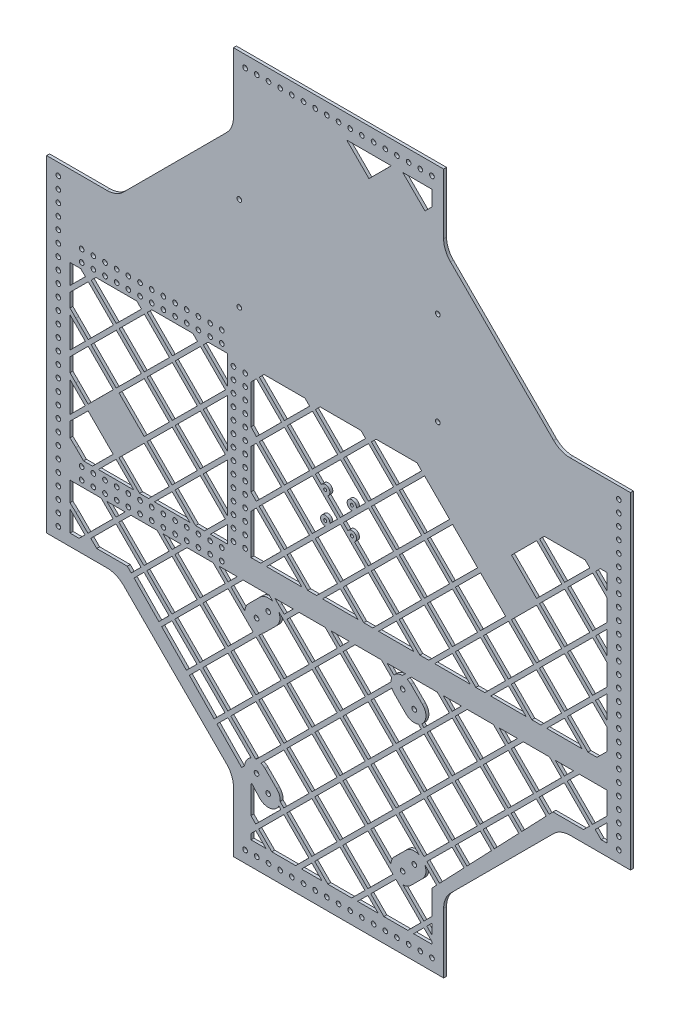
SolidWorks part; units mm, degrees
material "1060 Alloy"
ref_plane "Front Plane" through (0, 0, 0) normal (0, 0, 1) x (1, 0, 0)
ref_plane "Top Plane" through (0, 0, 0) normal (0, 1, 0) x (1, 0, 0)
ref_plane "Right Plane" through (0, 0, 0) normal (1, 0, 0) x (0, 0, -1)
sketch "Sketch1" plane through (0, 0, 0) normal (0, 0, 1) x (1, 0, 0)
  line L0 (-317.5, 177.8) -> (-317.5, -177.8)
  line L1 (-317.5, 381) -> (317.5, 381)
  line L2 (-317.5, 381) -> (-317.5, -381)
  line L3 (-317.5, -381) -> (317.5, -381)
  line L4 (317.5, 381) -> (317.5, -381)
  line L5 (-317.5, 381) -> (317.5, -381) construction
  line L6 (-317.5, -381) -> (317.5, 381) construction
  line L7 (317.5, 177.8) -> (317.5, -177.8)
  line L8 (-114.3, 381) -> (114.3, 381)
  line L9 (-114.3, -381) -> (114.3, -381)
  line L10 (-317.5, -177.8) -> (-241.3, -177.8)
  line L11 (-317.5, 177.8) -> (-241.3, 177.8)
  line L12 (-114.3, 381) -> (-114.3, 304.8)
  line L13 (114.3, 381) -> (114.3, 304.8)
  line L14 (317.5, 177.8) -> (241.3, 177.8)
  line L15 (317.5, -177.8) -> (241.3, -177.8)
  line L16 (114.3, -381) -> (114.3, -304.8)
  line L17 (-114.3, -381) -> (-114.3, -304.8)
  line L18 (-241.3, 177.8) -> (-114.3, 304.8)
  line L19 (114.3, 304.8) -> (241.3, 177.8)
  line L20 (114.3, -304.8) -> (241.3, -177.8)
  line L21 (-114.3, -304.8) -> (-241.3, -177.8)
  point P0 (0, 0)
  point P9 (-317.5, 0)
  point P12 (317.5, 0)
  point P15 (0, 381)
  point P18 (0, -381)
  dimension "D1" = 635
  dimension "D2" = 762
  dimension "D3" = 355.6
  dimension "D4" = 228.6
  dimension "D5" = 228.6
  dimension "D6" = 76.2
  dimension "D7" = 76.2
  dimension "D8" = 76.2
  dimension "D9" = 76.2
  dimension "D10" = 76.2
  dimension "D11" = 76.2
  dimension "D12" = 76.2
  dimension "D13" = 76.2
extrude "Boss-Extrude1" add sketch "Sketch1" along normal blind 3.175 contours L21 L17 L3 L16 L20 L15 L4 L14 L19 L13 L1 L12 L18 L11 L0 L10 region at (0, 0, 0)
sketch "Sketch2" plane through (0, 0, 3.175) normal (0, 0, 1) x (1, 0, 0)
  line L0 (-317.5, 177.8) -> (-317.5, -177.8) construction
  line L1 (-317.5, 177.8) -> (-241.3, 177.8) construction
  line L2 (-304.8, 177.8) -> (-304.8, -177.8) construction
  line L3 (-317.5, -177.8) -> (-241.3, -177.8) construction
  line L4 (0, 381) -> (0, -381) construction
  line L5 (-114.3, 381) -> (114.3, 381) construction
  line L6 (-114.3, -381) -> (114.3, -381) construction
  line L7 (-317.5, 0) -> (317.5, 0) construction
  line L8 (317.5, 177.8) -> (317.5, -177.8) construction
  line L9 (-114.3, -381) -> (-114.3, -304.8) construction
  line L10 (-114.3, -368.3) -> (114.3, -368.3) construction
  line L11 (114.3, -381) -> (114.3, -304.8) construction
  line L12 (-304.8, 165.1) -> (-292.1, 165.1) construction
  line L13 (-292.1, 165.1) -> (-292.1, -177.8) construction
  line L14 (317.5, 165.1) -> (272.8241, 165.1) construction
  line L15 (292.1, 177.8) -> (292.1, -177.8) construction
  line L16 (317.5, 177.8) -> (241.3, 177.8) construction
  line L17 (317.5, -177.8) -> (241.3, -177.8) construction
  line L18 (279.4, 177.8) -> (279.4, -177.8) construction
  line L19 (-101.6, -381) -> (-101.6, -331.9568) construction
  line L20 (-114.3, -342.9) -> (114.3, -342.9) construction
  line L21 (-114.3, -355.6) -> (114.3, -355.6) construction
  line L22 (-101.6, 381) -> (-101.6, 343.8859) construction
  line L23 (-114.3, 342.9) -> (114.3, 342.9) construction
  line L24 (-114.3, 381) -> (-114.3, 304.8) construction
  line L25 (114.3, 381) -> (114.3, 304.8) construction
  line L26 (-114.3, 355.6) -> (114.3, 355.6) construction
  circle A0 centre (-304.8, 165.1) radius 2.54
  circle A1 centre (-304.8, 152.4) radius 2.54
  circle A2 centre (-304.8, 139.7) radius 2.54
  circle A3 centre (-304.8, 127) radius 2.54
  circle A4 centre (-304.8, 114.3) radius 2.54
  circle A5 centre (-304.8, 101.6) radius 2.54
  circle A6 centre (-304.8, 88.9) radius 2.54
  circle A7 centre (-304.8, 76.2) radius 2.54
  circle A8 centre (-304.8, 63.5) radius 2.54
  circle A9 centre (-304.8, 50.8) radius 2.54
  circle A10 centre (-304.8, 38.1) radius 2.54
  circle A11 centre (-304.8, 25.4) radius 2.54
  circle A12 centre (-304.8, 12.7) radius 2.54
  circle A13 centre (-304.8, 0) radius 2.54
  circle A14 centre (-304.8, -12.7) radius 2.54
  circle A15 centre (-304.8, -25.4) radius 2.54
  circle A16 centre (-304.8, -38.1) radius 2.54
  circle A17 centre (-304.8, -50.8) radius 2.54
  circle A18 centre (-304.8, -63.5) radius 2.54
  circle A19 centre (-304.8, -76.2) radius 2.54
  circle A20 centre (-304.8, -88.9) radius 2.54
  circle A21 centre (-304.8, -101.6) radius 2.54
  circle A22 centre (-304.8, -114.3) radius 2.54
  circle A23 centre (-304.8, -127) radius 2.54
  circle A24 centre (-304.8, -139.7) radius 2.54
  circle A25 centre (-304.8, -152.4) radius 2.54
  circle A26 centre (-304.8, -165.1) radius 2.54
  circle A27 centre (304.8, -165.1) radius 2.54
  circle A28 centre (304.8, -152.4) radius 2.54
  circle A29 centre (304.8, -139.7) radius 2.54
  circle A30 centre (304.8, -127) radius 2.54
  circle A31 centre (304.8, -114.3) radius 2.54
  circle A32 centre (304.8, -101.6) radius 2.54
  circle A33 centre (304.8, -88.9) radius 2.54
  circle A34 centre (304.8, -76.2) radius 2.54
  circle A35 centre (304.8, -63.5) radius 2.54
  circle A36 centre (304.8, -50.8) radius 2.54
  circle A37 centre (304.8, -38.1) radius 2.54
  circle A38 centre (304.8, -25.4) radius 2.54
  circle A39 centre (304.8, -12.7) radius 2.54
  circle A40 centre (304.8, 0) radius 2.54
  circle A41 centre (304.8, 12.7) radius 2.54
  circle A42 centre (304.8, 25.4) radius 2.54
  circle A43 centre (304.8, 38.1) radius 2.54
  circle A44 centre (304.8, 50.8) radius 2.54
  circle A45 centre (304.8, 63.5) radius 2.54
  circle A46 centre (304.8, 76.2) radius 2.54
  circle A47 centre (304.8, 88.9) radius 2.54
  circle A48 centre (304.8, 101.6) radius 2.54
  circle A49 centre (304.8, 114.3) radius 2.54
  circle A50 centre (304.8, 127) radius 2.54
  circle A51 centre (304.8, 139.7) radius 2.54
  circle A52 centre (304.8, 152.4) radius 2.54
  circle A53 centre (304.8, 165.1) radius 2.54
  circle A54 centre (-101.6, -368.3) radius 2.54
  circle A55 centre (-88.9, -368.3) radius 2.54
  circle A56 centre (-76.2, -368.3) radius 2.54
  circle A57 centre (-63.5, -368.3) radius 2.54
  circle A58 centre (-50.8, -368.3) radius 2.54
  circle A59 centre (-38.1, -368.3) radius 2.54
  circle A60 centre (-25.4, -368.3) radius 2.54
  circle A61 centre (-12.7, -368.3) radius 2.54
  circle A62 centre (0, -368.3) radius 2.54
  circle A63 centre (12.7, -368.3) radius 2.54
  circle A64 centre (25.4, -368.3) radius 2.54
  circle A65 centre (38.1, -368.3) radius 2.54
  circle A66 centre (50.8, -368.3) radius 2.54
  circle A67 centre (63.5, -368.3) radius 2.54
  circle A68 centre (76.2, -368.3) radius 2.54
  circle A69 centre (88.9, -368.3) radius 2.54
  circle A70 centre (101.6, -368.3) radius 2.54
  circle A71 centre (101.6, 368.3) radius 2.54
  circle A72 centre (88.9, 368.3) radius 2.54
  circle A73 centre (76.2, 368.3) radius 2.54
  circle A74 centre (63.5, 368.3) radius 2.54
  circle A75 centre (50.8, 368.3) radius 2.54
  circle A76 centre (38.1, 368.3) radius 2.54
  circle A77 centre (25.4, 368.3) radius 2.54
  circle A78 centre (12.7, 368.3) radius 2.54
  circle A79 centre (0, 368.3) radius 2.54
  circle A80 centre (-12.7, 368.3) radius 2.54
  circle A81 centre (-25.4, 368.3) radius 2.54
  circle A82 centre (-38.1, 368.3) radius 2.54
  circle A83 centre (-50.8, 368.3) radius 2.54
  circle A84 centre (-63.5, 368.3) radius 2.54
  circle A85 centre (-76.2, 368.3) radius 2.54
  circle A86 centre (-88.9, 368.3) radius 2.54
  circle A87 centre (-101.6, 368.3) radius 2.54
  circle A115 centre (292.1, 165.1) radius 2.54
  circle A116 centre (279.4, 165.1) radius 2.54
  circle A117 centre (279.4, 152.4) radius 2.54
  circle A118 centre (292.1, 152.4) radius 2.54
  circle A119 centre (279.4, 139.7) radius 2.54
  circle A120 centre (292.1, 139.7) radius 2.54
  circle A121 centre (279.4, 127) radius 2.54
  circle A122 centre (292.1, 127) radius 2.54
  circle A123 centre (279.4, 114.3) radius 2.54
  circle A124 centre (292.1, 114.3) radius 2.54
  circle A125 centre (279.4, 101.6) radius 2.54
  circle A126 centre (292.1, 101.6) radius 2.54
  circle A127 centre (279.4, 88.9) radius 2.54
  circle A128 centre (292.1, 88.9) radius 2.54
  circle A129 centre (279.4, 76.2) radius 2.54
  circle A130 centre (292.1, 76.2) radius 2.54
  circle A131 centre (279.4, 63.5) radius 2.54
  circle A132 centre (292.1, 63.5) radius 2.54
  circle A133 centre (279.4, 50.8) radius 2.54
  circle A134 centre (292.1, 50.8) radius 2.54
  circle A135 centre (279.4, 38.1) radius 2.54
  circle A136 centre (292.1, 38.1) radius 2.54
  circle A137 centre (279.4, 25.4) radius 2.54
  circle A138 centre (292.1, 25.4) radius 2.54
  circle A139 centre (279.4, 12.7) radius 2.54
  circle A140 centre (292.1, 12.7) radius 2.54
  circle A141 centre (279.4, 0) radius 2.54
  circle A142 centre (292.1, 0) radius 2.54
  circle A143 centre (279.4, -12.7) radius 2.54
  circle A144 centre (292.1, -12.7) radius 2.54
  circle A145 centre (279.4, -25.4) radius 2.54
  circle A146 centre (292.1, -25.4) radius 2.54
  circle A147 centre (279.4, -38.1) radius 2.54
  circle A148 centre (292.1, -38.1) radius 2.54
  circle A149 centre (279.4, -50.8) radius 2.54
  circle A150 centre (292.1, -50.8) radius 2.54
  circle A151 centre (279.4, -63.5) radius 2.54
  circle A152 centre (292.1, -63.5) radius 2.54
  circle A153 centre (279.4, -76.2) radius 2.54
  circle A154 centre (292.1, -76.2) radius 2.54
  circle A155 centre (279.4, -88.9) radius 2.54
  circle A156 centre (292.1, -88.9) radius 2.54
  circle A157 centre (279.4, -101.6) radius 2.54
  circle A158 centre (292.1, -101.6) radius 2.54
  circle A159 centre (279.4, -114.3) radius 2.54
  circle A160 centre (292.1, -114.3) radius 2.54
  circle A161 centre (279.4, -127) radius 2.54
  circle A162 centre (292.1, -127) radius 2.54
  circle A163 centre (279.4, -139.7) radius 2.54
  circle A164 centre (292.1, -139.7) radius 2.54
  circle A165 centre (279.4, -152.4) radius 2.54
  circle A166 centre (292.1, -152.4) radius 2.54
  circle A167 centre (279.4, -165.1) radius 2.54
  circle A168 centre (292.1, -165.1) radius 2.54
  circle A169 centre (-101.6, -355.6) radius 2.54
  circle A170 centre (-101.6, -342.9) radius 2.54
  circle A171 centre (-88.9, -342.9) radius 2.54
  circle A172 centre (-88.9, -355.6) radius 2.54
  circle A173 centre (-76.2, -342.9) radius 2.54
  circle A174 centre (-76.2, -355.6) radius 2.54
  circle A175 centre (-63.5, -342.9) radius 2.54
  circle A176 centre (-63.5, -355.6) radius 2.54
  circle A177 centre (-50.8, -342.9) radius 2.54
  circle A178 centre (-50.8, -355.6) radius 2.54
  circle A179 centre (-38.1, -342.9) radius 2.54
  circle A180 centre (-38.1, -355.6) radius 2.54
  circle A181 centre (-25.4, -342.9) radius 2.54
  circle A182 centre (-25.4, -355.6) radius 2.54
  circle A183 centre (-12.7, -342.9) radius 2.54
  circle A184 centre (-12.7, -355.6) radius 2.54
  circle A185 centre (0, -342.9) radius 2.54
  circle A186 centre (0, -355.6) radius 2.54
  circle A187 centre (12.7, -342.9) radius 2.54
  circle A188 centre (12.7, -355.6) radius 2.54
  circle A189 centre (25.4, -342.9) radius 2.54
  circle A190 centre (25.4, -355.6) radius 2.54
  circle A191 centre (38.1, -342.9) radius 2.54
  circle A192 centre (38.1, -355.6) radius 2.54
  circle A193 centre (50.8, -342.9) radius 2.54
  circle A194 centre (50.8, -355.6) radius 2.54
  circle A195 centre (63.5, -342.9) radius 2.54
  circle A196 centre (63.5, -355.6) radius 2.54
  circle A197 centre (76.2, -342.9) radius 2.54
  circle A198 centre (76.2, -355.6) radius 2.54
  circle A199 centre (88.9, -342.9) radius 2.54
  circle A200 centre (88.9, -355.6) radius 2.54
  circle A201 centre (101.6, -342.9) radius 2.54
  circle A202 centre (101.6, -355.6) radius 2.54
  circle A203 centre (-101.6, 355.6) radius 2.54
  circle A204 centre (-101.6, 342.9) radius 2.54
  circle A205 centre (-88.9, 342.9) radius 2.54
  circle A206 centre (-88.9, 355.6) radius 2.54
  circle A207 centre (-76.2, 342.9) radius 2.54
  circle A208 centre (-76.2, 355.6) radius 2.54
  circle A209 centre (-63.5, 342.9) radius 2.54
  circle A210 centre (-63.5, 355.6) radius 2.54
  circle A211 centre (-50.8, 342.9) radius 2.54
  circle A212 centre (-50.8, 355.6) radius 2.54
  circle A213 centre (-38.1, 342.9) radius 2.54
  circle A214 centre (-38.1, 355.6) radius 2.54
  circle A215 centre (-25.4, 342.9) radius 2.54
  circle A216 centre (-25.4, 355.6) radius 2.54
  circle A217 centre (-12.7, 342.9) radius 2.54
  circle A218 centre (-12.7, 355.6) radius 2.54
  circle A219 centre (0, 342.9) radius 2.54
  circle A220 centre (0, 355.6) radius 2.54
  circle A221 centre (12.7, 342.9) radius 2.54
  circle A222 centre (12.7, 355.6) radius 2.54
  circle A223 centre (25.4, 342.9) radius 2.54
  circle A224 centre (25.4, 355.6) radius 2.54
  circle A225 centre (38.1, 342.9) radius 2.54
  circle A226 centre (38.1, 355.6) radius 2.54
  circle A227 centre (50.8, 342.9) radius 2.54
  circle A228 centre (50.8, 355.6) radius 2.54
  circle A229 centre (63.5, 342.9) radius 2.54
  circle A230 centre (63.5, 355.6) radius 2.54
  circle A231 centre (76.2, 342.9) radius 2.54
  circle A232 centre (76.2, 355.6) radius 2.54
  circle A233 centre (88.9, 342.9) radius 2.54
  circle A234 centre (88.9, 355.6) radius 2.54
  circle A235 centre (101.6, 342.9) radius 2.54
  circle A236 centre (101.6, 355.6) radius 2.54
  dimension "D1" = 5.08
  dimension "D5" = 5.08
  dimension "D2" = 12.7
  dimension "D3" = 12.7
  dimension "D6" = 12.7
  dimension "D7" = 12.7
  dimension "D9" = 12.7
  dimension "D4" = 27
  dimension "D8" = 17
  dimension "D11" = 3
  dimension "D12" = 27
  dimension "D13" = 3
  dimension "D14" = 17
  dimension "D15" = 3
  dimension "D16" = 17
extrude "Cut-Extrude2" cut sketch "Sketch2" against normal blind 3.175 contours A87 | A86 | A85 | A84 | A83 | A82 | A80 | A81 | A79 | A78 | A77 | A76 | A75 | A74 | A73 | A72 | A71 | A53 | A52 | A51 | A50 | A49 | A48 | A47 | A46 | A45 | A44 | A43 | A42 | A41 | A40 | A39 | A38 | A37 | A36 | A35 | A34 | A33 | A32 | A31 | A30 | A29 | A28 | A27 | A70 | A69 | A68 | A67 | A66 | A65 | A64 | A63 | A62 | A61 | A60 | A59 | A58 | A56 | A57 | A55 | A54 | A26 | A25 | A24 | A23 | A22 | A21 | A20 | A19 | A18 | A17 | A16 | A15 | A14 | A13 | A12 | A11 | A10 | A9 | A8 | A7 | A0 | A1 | A2 | A3 | A4 | A5 | A6
sketch "Sketch3" plane through (0, 0, 3.175) normal (0, 0, 1) x (1, 0, 0)
  line L0 (-317.5, 177.8) -> (-317.5, -177.8) construction
  line L1 (-14.478, 14.478) -> (14.478, 14.478)
  line L2 (-14.478, 14.478) -> (-14.478, -14.478)
  line L3 (-14.478, -14.478) -> (14.478, -14.478)
  line L4 (14.478, 14.478) -> (14.478, -14.478)
  line L5 (-14.478, 14.478) -> (14.478, -14.478) construction
  line L6 (-14.478, -14.478) -> (14.478, 14.478) construction
  line L7 (-107.95, 241.3) -> (107.95, 241.3)
  line L8 (-107.95, 241.3) -> (-107.95, 139.7)
  line L9 (-107.95, 139.7) -> (107.95, 139.7)
  line L10 (107.95, 241.3) -> (107.95, 139.7)
  line L11 (-107.95, 241.3) -> (107.95, 139.7) construction
  line L12 (-107.95, 139.7) -> (107.95, 241.3) construction
  line L14 (-114.3, 381) -> (114.3, 381) construction
  circle A0 centre (-14.478, 14.478) radius 1.651
  circle A1 centre (14.478, 14.478) radius 1.651
  circle A2 centre (14.478, -14.478) radius 1.651
  circle A3 centre (-14.478, -14.478) radius 1.651
  circle A4 centre (-107.95, 241.3) radius 2.54
  circle A5 centre (107.95, 241.3) radius 2.54
  circle A6 centre (107.95, 139.7) radius 2.54
  circle A7 centre (-107.95, 139.7) radius 2.54
  point P0 (0, 0)
  point P10 (0, 190.5)
  dimension "D6" = 5.08
  dimension "D7" = 5.08
  dimension "D8" = 5.08
  dimension "D9" = 5.08
  dimension "D11" = 3.302
  dimension "D12" = 3.302
  dimension "D13" = 3.302
  dimension "D14" = 3.302
  dimension "D1" = 28.956
  dimension "D2" = 28.956
  dimension "D3" = 215.9
  dimension "D4" = 101.6
  dimension "D5" = 209.55
  dimension "D10" = 241.3
extrude "Cut-Extrude3" cut sketch "Sketch3" against normal blind 3.175 contours L10 A5 L7 | L8 A7 L9 | L7 A4 L8 | L8 A4 L7 | L9 A7 L8 | L9 A6 L10 | L10 A6 L9 | L7 A5 L10 | A6 | A0 | A1 | A2 | A3 region at (-108.3093, 241.6593, 3.175) region at (-106.872, 240.222, 3.175) region at (108.3093, 241.6593, 3.175) region at (106.872, 240.222, 3.175) region at (-106.872, 140.778, 3.175) region at (-108.3093, 139.3407, 3.175) region at (108.3093, 139.3407, 3.175) region at (106.872, 140.778, 3.175)
sketch "Sketch4" plane through (0, 0, 3.175) normal (0, 0, 1) x (1, 0, 0)
  line L0 (-292.1, 177.8) -> (-292.1, -177.8) construction
  line L1 (-317.5, 177.8) -> (-241.3, 177.8) construction
  line L2 (-317.5, -177.8) -> (-241.3, -177.8) construction
  line L3 (-317.5, 177.8) -> (-317.5, -177.8) construction
  line L4 (-292.1, 83.439) -> (-292.1, 96.139) construction
  line L5 (-292.1, 83.439) -> (-110.998, 83.439)
  line L7 (-292.1, -83.439) -> (-110.998, -83.439)
  line L8 (-110.998, 83.439) -> (-110.998, -83.439)
  line L9 (-292.1, 96.139) -> (-98.298, 96.139) construction
  line L10 (-98.298, 96.139) -> (-98.298, -96.139) construction
  line L11 (-98.298, -96.139) -> (-292.1, -96.139) construction
  line L12 (-292.1, 96.139) -> (-279.4, 96.139) construction
  line L13 (-317.5, 0) -> (317.5, 0) construction
  line L14 (317.5, 177.8) -> (317.5, -177.8) construction
  line L15 (-292.1, 108.839) -> (-85.598, 108.839) construction
  line L16 (-85.598, 108.839) -> (-85.598, -108.839) construction
  line L17 (-85.598, -108.839) -> (-292.1, -108.839) construction
  line L18 (-114.3, 96.139) -> (-114.3, -96.139) construction
  line L19 (-114.3, -71.501) -> (-114.3, -84.201) construction
  line L20 (-101.6, -86.741) -> (-101.6, 96.139) construction
  line L21 (-114.3, -84.201) -> (-101.6, -84.201) construction
  circle A0 centre (-279.4, 96.139) radius 2.54
  circle A1 centre (-266.7, 96.139) radius 2.54
  circle A2 centre (-254, 96.139) radius 2.54
  circle A3 centre (-241.3, 96.139) radius 2.54
  circle A4 centre (-228.6, 96.139) radius 2.54
  circle A5 centre (-215.9, 96.139) radius 2.54
  circle A6 centre (-203.2, 96.139) radius 2.54
  circle A7 centre (-190.5, 96.139) radius 2.54
  circle A8 centre (-177.8, 96.139) radius 2.54
  circle A9 centre (-165.1, 96.139) radius 2.54
  circle A10 centre (-152.4, 96.139) radius 2.54
  circle A11 centre (-139.7, 96.139) radius 2.54
  circle A12 centre (-127, 96.139) radius 2.54
  circle A15 centre (-127, -96.139) radius 2.54
  circle A16 centre (-139.7, -96.139) radius 2.54
  circle A17 centre (-152.4, -96.139) radius 2.54
  circle A18 centre (-165.1, -96.139) radius 2.54
  circle A19 centre (-177.8, -96.139) radius 2.54
  circle A20 centre (-190.5, -96.139) radius 2.54
  circle A21 centre (-203.2, -96.139) radius 2.54
  circle A22 centre (-215.9, -96.139) radius 2.54
  circle A23 centre (-228.6, -96.139) radius 2.54
  circle A24 centre (-241.3, -96.139) radius 2.54
  circle A25 centre (-254, -96.139) radius 2.54
  circle A26 centre (-266.7, -96.139) radius 2.54
  circle A27 centre (-279.4, -96.139) radius 2.54
  circle A44 centre (-279.4, -108.839) radius 2.54
  circle A48 centre (-279.4, 108.839) radius 2.54
  circle A49 centre (-266.7, 108.839) radius 2.54
  circle A50 centre (-254, 108.839) radius 2.54
  circle A51 centre (-241.3, 108.839) radius 2.54
  circle A52 centre (-228.6, 108.839) radius 2.54
  circle A53 centre (-215.9, 108.839) radius 2.54
  circle A54 centre (-203.2, 108.839) radius 2.54
  circle A55 centre (-190.5, 108.839) radius 2.54
  circle A56 centre (-177.8, 108.839) radius 2.54
  circle A57 centre (-165.1, 108.839) radius 2.54
  circle A58 centre (-152.4, 108.839) radius 2.54
  circle A59 centre (-139.7, 108.839) radius 2.54
  circle A60 centre (-127, 108.839) radius 2.54
  circle A78 centre (-127, -108.839) radius 2.54
  circle A79 centre (-139.7, -108.839) radius 2.54
  circle A80 centre (-152.4, -108.839) radius 2.54
  circle A81 centre (-165.1, -108.839) radius 2.54
  circle A82 centre (-177.8, -108.839) radius 2.54
  circle A83 centre (-190.5, -108.839) radius 2.54
  circle A84 centre (-203.2, -108.839) radius 2.54
  circle A85 centre (-215.9, -108.839) radius 2.54
  circle A86 centre (-228.6, -108.839) radius 2.54
  circle A87 centre (-241.3, -108.839) radius 2.54
  circle A88 centre (-254, -108.839) radius 2.54
  circle A89 centre (-266.7, -108.839) radius 2.54
  circle A90 centre (-114.3, 108.839) radius 2.54 [skipped]
  circle A91 centre (-114.3, 80.899) radius 2.54
  circle A104 centre (-114.3, 68.199) radius 2.54
  circle A106 centre (-101.6, -84.201) radius 2.54
  circle A107 centre (-101.6, -71.501) radius 2.54
  circle A108 centre (-101.6, -58.801) radius 2.54
  circle A109 centre (-101.6, -46.101) radius 2.54
  circle A110 centre (-101.6, -33.401) radius 2.54
  circle A111 centre (-101.6, -20.701) radius 2.54
  circle A112 centre (-101.6, -8.001) radius 2.54
  circle A113 centre (-101.6, 4.699) radius 2.54
  circle A114 centre (-101.6, 17.399) radius 2.54
  circle A115 centre (-101.6, 30.099) radius 2.54
  circle A116 centre (-101.6, 42.799) radius 2.54
  circle A117 centre (-101.6, 55.499) radius 2.54
  circle A118 centre (-101.6, 68.199) radius 2.54
  circle A119 centre (-101.6, 80.899) radius 2.54
  circle A120 centre (-114.3, 55.499) radius 2.54
  circle A121 centre (-114.3, 42.799) radius 2.54
  circle A122 centre (-114.3, 30.099) radius 2.54
  circle A123 centre (-114.3, 17.399) radius 2.54
  circle A124 centre (-114.3, 4.699) radius 2.54
  circle A125 centre (-114.3, -8.001) radius 2.54
  circle A126 centre (-114.3, -20.701) radius 2.54
  circle A127 centre (-114.3, -33.401) radius 2.54
  circle A128 centre (-114.3, -46.101) radius 2.54
  circle A129 centre (-114.3, -58.801) radius 2.54
  circle A130 centre (-114.3, -71.501) radius 2.54
  circle A131 centre (-114.3, -84.201) radius 2.54
  dimension "D9" = 5.08
  dimension "D14" = 12.7
  dimension "D17" = 14
  dimension "D11" = 14
  dimension "D1" = 25.4
  dimension "D2" = 181.102
  dimension "D3" = 12.7
  dimension "D4" = 94.361
  dimension "D5" = 12.7
  dimension "D6" = 12.7
  dimension "D7" = 12.7
  dimension "D8" = 12.7
  dimension "D15" = 12.7
  dimension "D16" = 12.7
  dimension "D10" = 14
extrude "Cut-Extrude5" cut sketch "Sketch4" against normal blind 3.175 contours A44 | A26 | A25 | A88 | A89 | A24 | A87 | A86 | A23 | A22 | A21 | A20 | A19 | A18 | A17 | A16 | A15 | A119 | A78 | A79 | A80 | A81 | A82 | A83 | A84 | A85 | A60 | A59 | A58 | A57 | A56 | A55 | A54 | A53 | A5 | A6 | A7 | A8 | A9 | A10 | A12 | A0 | A48 | A49 | A50 | A51 | A52 | A4 | A2 | A1 | A89 | A78 | A3 | A11 | A91 | A104 | A118 | A120 | A117 | A121 | A116 | A122 | A115 | A123 | A114 | A124 | A113 | A125 | A112 | A111 | A126 | A131 | A106 | A107 | A130 | A108 | A129 | A128 | A109 | A110 | A127 | A27 region at (-279.4, 96.139, 3.175) region at (-266.7, 96.139, 3.175) region at (-254, 96.139, 3.175) region at (-228.6, 96.139, 3.175) region at (-215.9, 96.139, 3.175) region at (-203.2, 96.139, 3.175) region at (-190.5, 96.139, 3.175) region at (-177.8, 96.139, 3.175) region at (-165.1, 96.139, 3.175) region at (-152.4, 96.139, 3.175) region at (-127, 96.139, 3.175) region at (-127, -96.139, 3.175) region at (-139.7, -96.139, 3.175) region at (-152.4, -96.139, 3.175) region at (-165.1, -96.139, 3.175) region at (-177.8, -96.139, 3.175) region at (-190.5, -96.139, 3.175) region at (-203.2, -96.139, 3.175) region at (-215.9, -96.139, 3.175) region at (-228.6, -96.139, 3.175) region at (-241.3, -96.139, 3.175) region at (-254, -96.139, 3.175) region at (-266.7, -96.139, 3.175) region at (-279.4, -108.839, 3.175) region at (-279.4, 108.839, 3.175) region at (-266.7, 108.839, 3.175) region at (-254, 108.839, 3.175) region at (-241.3, 108.839, 3.175) region at (-228.6, 108.839, 3.175) region at (-215.9, 108.839, 3.175) region at (-203.2, 108.839, 3.175) region at (-190.5, 108.839, 3.175) region at (-177.8, 108.839, 3.175) region at (-165.1, 108.839, 3.175) region at (-152.4, 108.839, 3.175) region at (-139.7, 108.839, 3.175) region at (-127, 108.839, 3.175) region at (-127, -108.839, 3.175) region at (-139.7, -108.839, 3.175) region at (-152.4, -108.839, 3.175) region at (-165.1, -108.839, 3.175) region at (-177.8, -108.839, 3.175) region at (-190.5, -108.839, 3.175) region at (-203.2, -108.839, 3.175) region at (-215.9, -108.839, 3.175) region at (-228.6, -108.839, 3.175) region at (-241.3, -108.839, 3.175) region at (-254, -108.839, 3.175) region at (-266.7, -108.839, 3.175) region at (-101.6, 80.899, 3.175)
sketch "Sketch5" plane through (0, 0, 3.175) normal (0, 0, 1) x (1, 0, 0)
  line L0 (-76.4928, -143.819) -> (-76.4928, -131.119) construction
  line L1 (-76.4928, -143.819) -> (69.6588, -143.819) construction
  line L2 (-76.4928, -143.819) -> (-76.4928, -289.9706) construction
  line L3 (-76.4928, -289.9706) -> (69.6588, -289.9706) construction
  line L4 (69.6588, -143.819) -> (69.6588, -289.9706) construction
  line L5 (-76.4928, -143.819) -> (69.6588, -289.9706) construction
  line L6 (-76.4928, -289.9706) -> (69.6588, -143.819) construction
  line L7 (-76.4928, -143.819) -> (-89.1928, -143.819) construction
  line L8 (82.3588, -143.819) -> (69.6588, -143.819) construction
  line L9 (69.6588, -143.819) -> (69.6588, -131.119) construction
  line L10 (69.6588, -289.9706) -> (82.3588, -289.9706) construction
  line L11 (-76.4928, -289.9706) -> (-89.1928, -289.9706) construction
  line L12 (-76.4928, -289.9706) -> (-76.4928, -302.6706) construction
  line L13 (69.6588, -289.9706) -> (69.6588, -302.6706) construction
  circle A0 centre (-76.4928, -131.119) radius 2.54
  circle A1 centre (-89.1928, -143.819) radius 2.54
  circle A2 centre (69.6588, -131.119) radius 2.54
  circle A3 centre (82.3588, -143.819) radius 2.54
  circle A4 centre (82.3588, -289.9706) radius 2.54
  circle A5 centre (69.6588, -302.6706) radius 2.54
  circle A6 centre (-76.4928, -302.6706) radius 2.54
  circle A7 centre (-89.1928, -289.9706) radius 2.54
  point P0 (-3.417, -216.8948)
  dimension "D5" = 12.7
  dimension "D1" = 146.1516
  dimension "D2" = 146.1516
  dimension "D3" = 12.7
  dimension "D4" = 12.7
  dimension "D6" = 12.7
  dimension "D7" = 12.7
  dimension "D8" = 12.7
  dimension "D9" = 12.7
  dimension "D10" = 12.7
extrude "Cut-Extrude7" cut sketch "Sketch5" against normal blind 3.175 contours A7 | A6 | A5 | A4 | A3 | A2 | A0 | A1
fillet "Fillet1" radius 25.4 1 edges at (-241.3, -177.8, 1.5875)
fillet "Fillet2" radius 25.4 1 edges at (-114.3, -304.8, 1.5875)
fillet "Fillet3" radius 25.4 2 edges at (114.3, -304.8, 1.5875) (241.3, -177.8, 1.5875)
fillet "Fillet4" radius 25.4 2 edges at (114.3, 304.8, 1.5875) (241.3, 177.8, 1.5875)
fillet "Fillet5" radius 25.4 2 edges at (-241.3, 177.8, 1.5875) (-114.3, 304.8, 1.5875)
sketch "Sketch7" plane through (0, 0, 3.175) normal (0, 0, 1) x (1, 0, 0)
  line L0 (317.5, -177.8) -> (251.821, -177.8) construction
  line L5 (-85.4947, -122.129) -> (-98.1848, -134.8457)
  line L6 (-80.2195, -152.8111) -> (-67.5028, -140.121)
  line L17 (72.6439, -281.8271) -> (60.2805, -294.092)
  line L18 (78.3535, -311.9349) -> (91.2495, -299.0068)
  line L23 (-80.0137, -280.786) -> (-67.3099, -293.4822)
  line L24 (-94.2842, -302.1031) -> (-85.7827, -311.7507)
  line L29 (-288.3685, 165.1) -> (-255.6803, 165.1)
  line L30 (-236.0395, 165.1) -> (-234.8989, 166.2406)
  line L35 (-101.6, 299.5395) -> (-101.6, 312.3295)
  line L36 (-317.5, 177.8) -> (-251.821, 177.8) construction
  line L41 (-233.8605, 185.2395) -> (-121.7395, 297.3605) construction
  line L42 (-114.3, 381) -> (-114.3, 315.321) construction
  line L47 (101.6, 355.6) -> (101.6, 338.909)
  line L48 (101.6, 299.5395) -> (112.1376, 288.6576)
  line L80 (-292.1, 162.4811) -> (-292.1, 128.8038)
  line L84 (292.1, 165.1) -> (292.1, 164.2432)
  line L85 (114.3, 381) -> (114.3, 315.321) construction
  line L90 (120.3017, -249.986) -> (93.0452, -222.7252)
  line L95 (231.7869, 165.1) -> (231.9997, 165.1)
  line L98 (317.5, 177.8) -> (251.821, 177.8) construction
  line L102 (233.1856, -165.1) -> (266.4365, -165.1)
  line L104 (101.6, -355.6) -> (101.6, -353.2207)
  line L107 (233.1856, -165.1) -> (229.0174, -169.4589)
  line L113 (-236.0395, -165.1) -> (-263.0209, -165.1)
  line L114 (-317.5, -177.8) -> (-251.821, -177.8) construction
  line L115 (101.6, 317.4457) -> (94.0203, 325.0266)
  line L116 (-95.25, -302.9542) -> (-95.25, -332.8975)
  line L117 (-59.3977, -246.8162) -> (-86.6542, -219.5554)
  line L118 (78.6391, -122.1388) -> (91.3391, -134.8388)
  line L125 (-292.1, -115.189) -> (-258.314, -115.189)
  line L127 (60.6786, -140.0993) -> (73.3786, -152.7993)
  line L129 (-120.65, 89.789) -> (-120.65, 58.3246)
  line L131 (-95.25, 75.6446) -> (-95.25, 33.4387)
  line L132 (266.4365, -165.1) -> (272.8642, -158.6941)
  line L133 (-78.9011, -355.6) -> (-90.0515, -344.4478)
  line L134 (253.9215, 165.1) -> (273.4059, 145.6125) construction
  line L135 (196.1124, -203.8694) -> (184.5394, -192.2946)
  line L136 (-89.4716, -33.7747) -> (-62.1449, -6.5408)
  line L137 (166.3116, -235.0336) -> (154.0052, -222.7252)
  line L139 (292.1, -55.9936) -> (276.2502, -40.1413)
  line L141 (14.3284, -355.6) -> (28.6992, -341.278)
  line L142 (-46.6316, -355.6) -> (-32.2608, -341.278)
  line L145 (292.1, 65.9496) -> (276.4688, 81.5832)
  line L146 (43.0189, -355.6) -> (31.8685, -344.4478)
  line L147 (75.2884, -355.6) -> (89.6592, -341.278)
  line L148 (-64.5323, 355.6) -> (-88.8484, 331.3663) construction
  line L149 (-292.1, -53.4562) -> (-275.5591, -36.9714)
  line L150 (-72.5511, -355.6) -> (-46.6316, -355.6)
  line L151 (-292.1, 68.0504) -> (-275.3424, 84.7512)
  line L152 (-292.1, 7.2834) -> (-275.4439, 23.883)
  line L153 (-292.1, 128.8038) -> (-275.2341, 145.6125)
  line L154 (292.1, 126.9155) -> (276.5753, 142.4427)
  line L155 (-255.6803, 165.1) -> (-272.0534, 148.7824) construction
  line L156 (-292.1, -142.3673) -> (-292.1, -165.1)
  line L157 (-206.6364, -89.789) -> (-184.1733, -67.4021)
  line L159 (-222.7499, -89.789) -> (-241.9639, -70.5719)
  line L160 (-101.6, 318.6579) -> (-92.029, 328.1965)
  line L161 (-145.6764, -89.789) -> (-123.2133, -67.4021)
  line L162 (-161.7899, -89.789) -> (-181.0039, -70.5719)
  line L163 (-84.7164, -89.789) -> (-62.2533, -67.4021)
  line L165 (-123.2133, -67.4021) -> (-150.4698, -40.1413)
  line L166 (-23.7564, -89.789) -> (-1.2933, -67.4021)
  line L167 (-39.8699, -89.789) -> (-59.0839, -70.5719)
  line L168 (37.2036, -89.789) -> (59.6667, -67.4021)
  line L169 (21.0901, -89.789) -> (1.8761, -70.5719)
  line L170 (98.1636, -89.789) -> (120.6267, -67.4021)
  line L171 (82.0501, -89.789) -> (62.8361, -70.5719)
  line L172 (159.1236, -89.789) -> (181.5867, -67.4021)
  line L173 (143.0101, -89.789) -> (123.7961, -70.5719)
  line L174 (-95.25, -302.9542) -> (-94.2842, -302.1031)
  line L175 (220.0836, -89.789) -> (242.5471, -67.4017)
  line L176 (225.9131, -172.7052) -> (215.0736, -161.8639)
  line L178 (203.9701, -89.789) -> (184.7561, -70.5719)
  line L179 (281.0436, -89.789) -> (292.1, -78.7701)
  line L180 (264.9309, -89.789) -> (245.7164, -70.5716)
  line L181 (-123.1049, -6.5408) -> (-150.3614, 20.72)
  line L182 (136.5109, -266.1978) -> (123.471, -253.1559)
  line L183 (292.1, 4.9761) -> (276.3586, 20.72)
  line L184 (106.7101, -297.362) -> (93.7418, -284.3916)
  line L185 (-89.3385, 27.1111) -> (-62.0366, 54.3205)
  line L186 (101.6, -353.2207) -> (92.8285, -344.4478)
  line L187 (-122.9966, 54.3205) -> (-150.2531, 81.5813)
  line L189 (-183.8414, 115.175) -> (-211.1047, 142.4427)
  line L190 (-17.9411, -355.6) -> (-29.0915, -344.4478)
  line L192 (-244.8082, 115.1819) -> (-272.0647, 142.4427)
  line L193 (-244.8082, 115.1819) -> (-244.8011, 115.189)
  line L195 (-122.8882, 115.1819) -> (-150.1447, 142.4427)
  line L196 (-89.6788, -276.9947) -> (-62.5783, -249.986)
  line L197 (-95.1144, -278.4144) -> (-120.369, -253.1559)
  line L198 (-135.3886, -261.7961) -> (-123.5383, -249.986)
  line L199 (-105.3426, -292.6053) -> (-102.167, -289.4405)
  line L201 (-165.4346, -230.9869) -> (-153.9642, -219.5554)
  line L202 (-195.4806, -200.1778) -> (-184.39, -189.1247)
  line L203 (-225.5266, -169.3686) -> (-214.8158, -158.6941)
  line L204 (-269.3709, -165.1) -> (-272.6064, -161.8639)
  line L205 (-282.2035, -165.1) -> (-275.7758, -158.6941)
  line L206 (-61.9282, 115.1819) -> (-89.1847, 142.4427)
  line L207 (-267.5964, -89.789) -> (-245.1333, -67.4021)
  line L209 (-180.5593, 179.213) -> (-153.2057, 206.4738)
  line L210 (-177.3899, 176.0432) -> (-150.0364, 203.304)
  line L211 (-180.5593, 179.213) -> (-198.0665, 196.723)
  line L212 (-0.9682, 115.1819) -> (-28.2247, 142.4427)
  line L214 (59.9918, 115.1819) -> (32.7352, 142.4426)
  line L215 (-183.7399, 176.0432) -> (-201.2417, 193.5478)
  line L216 (-150.0251, 209.6437) -> (-122.6716, 236.9045)
  line L217 (-153.2057, 206.4738) -> (-170.7593, 224.0302)
  line L218 (-150.0251, 209.6437) -> (-167.584, 227.2054)
  line L219 (-146.8557, 206.4738) -> (-119.5022, 233.7346)
  line L220 (-119.4909, 240.0743) -> (-92.1377, 267.3349)
  line L222 (120.9518, 115.1819) -> (93.6953, 142.4427)
  line L224 (238.3497, 165.1) -> (253.9215, 165.1)
  line L225 (181.9118, 115.1819) -> (154.6553, 142.4427)
  line L226 (242.8756, 115.1819) -> (188.2618, 115.1819)
  line L227 (242.8756, 115.1819) -> (215.6172, 142.4446)
  line L228 (108.2879, 249.7909) -> (93.9139, 264.1672)
  line L229 (-9.4044, -14.7323) -> (-1.1849, -6.5408)
  line L230 (19.5453, 14.1192) -> (29.3492, 23.8899)
  line L231 (-101.8875, -143.3499) -> (-116.9716, -128.2634)
  line L232 (-70.9713, -119.6523) -> (-75.434, -115.189)
  line L233 (57.8193, -126.524) -> (46.486, -115.189)
  line L234 (69.4342, -118.421) -> (72.6772, -115.189)
  line L235 (92.9481, -277.2468) -> (120.3017, -249.986)
  line L242 (-285.75, 165.1) -> (-255.6803, 165.1)
  line L243 (-228.5489, 166.2406) -> (-231.7239, 169.4156)
  line L244 (-92.029, 328.1965) -> (-95.25, 331.4179)
  line L245 (94.0316, 331.3663) -> (69.8018, 355.6)
  line L246 (276.5866, 148.7824) -> (292.1, 164.2432)
  line L247 (63.5945, 355.4572) -> (90.851, 328.1965) construction
  line L248 (-275.2341, 145.6125) -> (-292.1, 162.4811)
  line L249 (-7.8909, -19.5525) -> (-3.0544, -14.7323)
  line L250 (-101.6, 355.6) -> (-64.5323, 355.6)
  line L251 (-95.25, -355.6) -> (-78.9011, -355.6)
  line L253 (239.5356, -165.1) -> (266.4365, -165.1)
  line L254 (81.6384, -355.6) -> (101.6, -355.6)
  line L255 (184.659, -125.0935) -> (174.756, -115.189)
  line L256 (-132.2588, -265.0054) -> (-105.3426, -292.6053)
  line L257 (-229.6895, -165.1) -> (-263.0209, -165.1)
  line L258 (5.7068, 297.7658) -> (33.0622, 325.0285)
  line L265 (-277.3599, -89.789) -> (-267.5964, -89.789)
  line L267 (-285.75, -115.189) -> (-258.314, -115.189)
  line L268 (-122.6716, 236.9045) -> (-140.2769, 254.5126)
  line L273 (-95.25, -89.789) -> (-88.9, -89.789)
  line L275 (62.5223, -246.8162) -> (35.2658, -219.5554)
  line L276 (-72.5511, -355.6) -> (-86.8708, -341.278)
  line L277 (199.2166, -200.6231) -> (187.72, -189.1247)
  line L278 (-86.3291, -36.9714) -> (-58.9756, -9.7106)
  line L279 (169.4159, -231.7873) -> (157.1858, -219.5554)
  line L280 (292.1, -49.6425) -> (279.4309, -36.9714)
  line L281 (20.6784, -355.6) -> (31.8685, -344.4478)
  line L282 (-40.2816, -355.6) -> (-29.0915, -344.4478)
  line L283 (292.1019, 72.2987) -> (279.6495, 84.7531)
  line L284 (-119.4909, 240.0743) -> (-137.1016, 257.6879)
  line L285 (-116.3216, 236.9045) -> (-113.962, 239.256)
  line L286 (-92.2457, 206.4738) -> (-119.5022, 233.7346)
  line L287 (49.3689, -355.6) -> (35.0492, -341.278)
  line L288 (81.6384, -355.6) -> (92.8285, -344.4478)
  line L289 (-285.75, -53.4562) -> (-272.3898, -40.1413)
  line L290 (-95.25, -349.6287) -> (-90.0515, -344.4478)
  line L291 (-285.75, 68.0504) -> (-272.1731, 81.5813)
  line L292 (-285.7431, 7.2902) -> (-272.2745, 20.7132)
  line L293 (-285.75, 128.8038) -> (-272.0647, 142.4427)
  line L294 (292.1, 133.2665) -> (279.7559, 145.6125)
  line L295 (-277.3599, -89.789) -> (-285.75, -81.3976)
  line L296 (-200.2864, -89.789) -> (-181.0039, -70.5719)
  line L297 (-216.3999, -89.789) -> (-238.7833, -67.4021)
  line L298 (-95.25, 318.6579) -> (-88.8597, 325.0266)
  line L299 (-139.3264, -89.789) -> (-120.65, -71.176)
  line L300 (-155.4399, -89.789) -> (-177.8233, -67.4021)
  line L301 (-78.3664, -89.789) -> (-59.0839, -70.5719)
  line L302 (-120.65, -63.6148) -> (-147.2891, -36.9714)
  line L303 (-17.4064, -89.789) -> (1.8761, -70.5719)
  line L304 (-33.5199, -89.789) -> (-55.9033, -67.4021)
  line L305 (43.5536, -89.789) -> (62.8361, -70.5719)
  line L306 (27.4401, -89.789) -> (5.0567, -67.4021)
  line L307 (104.5136, -89.789) -> (123.7961, -70.5719)
  line L308 (88.4001, -89.789) -> (66.0167, -67.4021)
  line L309 (165.4736, -89.789) -> (184.7561, -70.5719)
  line L310 (149.3601, -89.789) -> (126.9767, -67.4021)
  line L311 (285.6191, -165.1) -> (279.2142, -158.6941)
  line L312 (226.4336, -89.789) -> (245.7164, -70.5716)
  line L313 (-89.0651, 209.6437) -> (-61.7118, 236.9043)
  line L314 (229.0174, -169.4589) -> (218.2542, -158.6941)
  line L315 (210.3201, -89.789) -> (187.9367, -67.4021)
  line L316 (21.1696, 9.4095) -> (25.8953, 14.1192)
  line L317 (271.2809, -89.789) -> (248.8971, -67.4017)
  line L318 (-31.5024, 84.7512) -> (-36.5394, 89.789)
  line L319 (139.6151, -262.9515) -> (126.6517, -249.986)
  line L320 (292.1, 11.3271) -> (279.5392, 23.8899)
  line L321 (109.8144, -294.1157) -> (96.1175, -280.4167)
  line L322 (-86.2208, 23.8899) -> (-58.8672, 51.1507)
  line L323 (35.0492, -341.278) -> (62.4027, -314.0172)
  line L324 (-62.2533, -67.4021) -> (-89.4672, -40.1839)
  line L326 (-11.5911, -355.6) -> (-25.9108, -341.278)
  line L327 (-177.4982, 115.1819) -> (-150.1447, 142.4427)
  line L329 (-238.4582, 115.1819) -> (-211.1047, 142.4427)
  line L330 (-116.5382, 115.1819) -> (-89.1847, 142.4427)
  line L332 (-83.3288, -276.9947) -> (-59.409, -253.1559)
  line L333 (-90.1572, -277.0214) -> (-117.1883, -249.986)
  line L334 (-132.2588, -265.0054) -> (-120.369, -253.1559)
  line L335 (56.9254, -302.188) -> (35.1575, -280.4167)
  line L336 (-55.5782, 115.1819) -> (-28.2247, 142.4427)
  line L337 (-162.3048, -234.1962) -> (-150.7948, -222.7252)
  line L338 (-192.3508, -203.387) -> (-181.2206, -192.2946)
  line L339 (-222.3969, -172.5779) -> (-211.6464, -161.8639)
  line L340 (-263.0209, -165.1) -> (-269.4258, -158.6941)
  line L341 (-275.8535, -165.1) -> (-272.6064, -161.8639)
  line L343 (-261.2464, -89.789) -> (-241.9639, -70.5719)
  line L344 (5.3818, 115.1819) -> (32.7352, 142.4426)
  line L346 (66.3418, 115.1819) -> (93.6953, 142.4427)
  line L348 (127.3018, 115.1819) -> (154.6553, 142.4427)
  line L349 (181.9118, 115.1819) -> (127.3018, 115.1819)
  line L350 (188.2618, 115.1819) -> (215.6172, 142.4446)
  line L351 (120.9518, 115.1819) -> (66.3418, 115.1819)
  line L352 (249.2237, 115.1838) -> (276.5753, 142.4427)
  line L353 (249.2237, 115.1838) -> (249.2184, 115.189)
  line L354 (117.8814, 246.5469) -> (97.0945, 267.337)
  line L355 (-3.0544, -14.7323) -> (1.9844, -9.7106)
  line L356 (25.8953, 14.1192) -> (32.5186, 20.72)
  line L357 (-56.0116, -128.2634) -> (-42.8928, -115.189)
  line L358 (-89.0651, 209.6437) -> (-116.3216, 236.9045)
  line L359 (-85.8957, 206.4738) -> (-58.5424, 233.7344)
  line L360 (-92.1377, 267.3349) -> (-109.7948, 284.9947)
  line L361 (-88.957, 270.5047) -> (-61.6032, 297.7658)
  line L362 (-88.957, 270.5047) -> (-106.6195, 288.1699)
  line L363 (-85.7877, 267.3349) -> (-58.4339, 294.5959)
  line L364 (-140.2769, 254.5126) -> (-143.4519, 257.6876)
  line L365 (-201.2417, 193.5478) -> (-204.4167, 196.7228)
  line L366 (-198.0665, 196.723) -> (-201.2415, 199.898)
  line L367 (-170.7593, 224.0302) -> (-173.9343, 227.2052)
  line L368 (-167.584, 227.2054) -> (-170.7588, 230.3807)
  line L369 (-109.7948, 284.9947) -> (-112.9698, 288.1697)
  line L370 (-137.1016, 257.6879) -> (-140.2766, 260.8629)
  line L371 (-106.6195, 288.1699) -> (-109.7945, 291.3449)
  line L372 (-95.25, 318.6579) -> (-101.6, 312.3295)
  line L373 (-92.029, 328.1965) -> (-101.6, 318.6579) construction
  line L374 (-64.6213, -119.6523) -> (-69.084, -115.189)
  line L375 (60.2427, -122.5969) -> (52.836, -115.189)
  line L376 (75.7842, -118.421) -> (79.0272, -115.189)
  line L377 (96.1175, -280.4167) -> (123.471, -253.1559)
  line L378 (260.2715, 165.1) -> (276.5866, 148.7824) construction
  line L379 (-58.3255, 355.4572) -> (-85.679, 328.1965) construction
  line L380 (-249.3303, 165.1) -> (-268.8841, 145.6125) construction
  line L381 (69.8018, 355.6) -> (94.0316, 331.3663) construction
  line L382 (-95.25, -293.8011) -> (-79.4327, -311.7507) [skipped]
  line L383 (-73.6637, -280.786) -> (-60.9599, -293.4822) [skipped]
  line L384 (-102.2128, -295.8146) -> (-100.9418, -294.548) [skipped]
  line L385 (78.9939, -281.8271) -> (66.6305, -294.092) [skipped]
  line L386 (87.9397, -278.5886) -> (62.511, -253.1559)
  line L387 (84.7035, -311.9349) -> (97.5995, -299.0068) [skipped]
  line L388 (92.8398, -338.1081) -> (101.6, -329.3776)
  line L389 (96.0092, -341.278) -> (101.6, -335.7061)
  line L390 (89.6592, -341.278) -> (62.4027, -314.0172)
  line L391 (92.8398, -338.1081) -> (70.1365, -315.4012)
  line L392 (101.6, -329.3776) -> (101.6, -302.7059)
  line L393 (101.6, -346.8697) -> (96.0092, -341.278)
  line L394 (101.6, -346.8697) -> (101.6, -335.7061)
  line L395 (110.3289, -355.6) -> (107.95, -353.2207) [skipped]
  line L396 (31.8798, -338.1081) -> (59.2333, -310.8473)
  line L397 (28.6992, -341.278) -> (1.4427, -314.0172)
  line L398 (31.8798, -338.1081) -> (4.6233, -310.8473)
  line L399 (59.2333, -310.8473) -> (31.9769, -283.5865)
  line L400 (31.9881, -277.2468) -> (59.3417, -249.986)
  line L401 (35.1575, -280.4167) -> (62.511, -253.1559)
  line L402 (28.8075, -280.4167) -> (1.551, -253.1559)
  line L403 (31.9881, -277.2468) -> (4.7317, -249.986)
  line L404 (1.454, -307.6775) -> (28.8075, -280.4167)
  line L405 (4.6233, -310.8473) -> (31.9769, -283.5865)
  line L406 (1.454, -307.6775) -> (-25.8025, -280.4167)
  line L407 (-1.7267, -310.8473) -> (-28.9831, -283.5865)
  line L408 (-29.0802, -338.1081) -> (-1.7267, -310.8473)
  line L409 (-25.9108, -341.278) -> (1.4427, -314.0172)
  line L410 (-32.2608, -341.278) -> (-59.5173, -314.0172)
  line L411 (-29.0802, -338.1081) -> (-56.3367, -310.8473)
  line L412 (92.9481, -277.2468) -> (65.6917, -249.986)
  line L413 (106.7101, -297.362) -> (101.6, -302.7059)
  line L414 (136.5109, -266.1978) -> (109.8144, -294.1157)
  line L415 (126.6517, -249.986) -> (154.0052, -222.7252)
  line L416 (123.4823, -246.8162) -> (150.8358, -219.5554)
  line L417 (123.4823, -246.8162) -> (96.2258, -219.5554)
  line L418 (150.8358, -219.5554) -> (123.5794, -192.2946)
  line L419 (154.0165, -216.3855) -> (181.37, -189.1247)
  line L420 (154.0165, -216.3855) -> (126.76, -189.1247)
  line L421 (157.1858, -219.5554) -> (184.5394, -192.2946)
  line L422 (166.3116, -235.0336) -> (139.6151, -262.9515)
  line L423 (181.37, -189.1247) -> (154.1136, -161.8639)
  line L424 (184.5507, -185.9548) -> (211.9042, -158.6941)
  line L425 (184.5507, -185.9548) -> (157.2942, -158.6941)
  line L426 (187.72, -189.1247) -> (215.0736, -161.8639)
  line L427 (196.1124, -203.8694) -> (169.4159, -231.7873)
  line L428 (211.9042, -158.6941) -> (184.6477, -131.4333)
  line L429 (215.0848, -155.5242) -> (242.4384, -128.2634)
  line L430 (215.0848, -155.5242) -> (187.8284, -128.2634)
  line L431 (218.2542, -158.6941) -> (245.6077, -131.4333)
  line L432 (225.9131, -172.7052) -> (199.2166, -200.6231)
  line L433 (272.8642, -158.6941) -> (245.6077, -131.4333)
  line L434 (276.0448, -155.5242) -> (292.1, -139.5235)
  line L435 (276.0448, -155.5242) -> (248.7884, -128.2634)
  line L436 (279.2142, -158.6941) -> (292.1, -145.8519)
  line L437 (292.1, -145.8519) -> (292.1, -165.1)
  line L438 (292.1, -115.189) -> (292.1, -139.5235)
  line L439 (29.3492, 23.8899) -> (2.0928, 51.1507)
  line L440 (32.5299, 27.0597) -> (59.8834, 54.3205)
  line L441 (242.4384, -128.2634) -> (229.366, -115.189)
  line L442 (245.619, -125.0935) -> (255.5572, -115.189)
  line L443 (245.619, -125.0935) -> (235.716, -115.189)
  line L444 (248.7884, -128.2634) -> (261.9072, -115.189)
  line L445 (181.4784, -128.2634) -> (168.406, -115.189)
  line L446 (184.659, -125.0935) -> (194.5972, -115.189)
  line L447 (187.8284, -128.2634) -> (200.9472, -115.189)
  line L448 (150.9442, -158.6941) -> (123.6877, -131.4333)
  line L449 (154.1248, -155.5242) -> (181.4784, -128.2634)
  line L450 (154.1248, -155.5242) -> (126.8684, -128.2634)
  line L451 (157.2942, -158.6941) -> (184.6477, -131.4333)
  line L452 (120.41, -189.1247) -> (93.1536, -161.8639)
  line L453 (123.5907, -185.9548) -> (150.9442, -158.6941)
  line L454 (123.5907, -185.9548) -> (96.3342, -158.6941)
  line L455 (126.76, -189.1247) -> (154.1136, -161.8639)
  line L456 (89.8758, -219.5554) -> (62.6194, -192.2946)
  line L457 (93.0565, -216.3855) -> (120.41, -189.1247)
  line L458 (93.0565, -216.3855) -> (65.8, -189.1247)
  line L459 (96.2258, -219.5554) -> (123.5794, -192.2946)
  line L460 (59.3417, -249.986) -> (32.0852, -222.7252)
  line L461 (62.5223, -246.8162) -> (89.8758, -219.5554)
  line L462 (65.6917, -249.986) -> (93.0452, -222.7252)
  line L463 (-90.0402, -338.1081) -> (-62.6867, -310.8473)
  line L464 (-90.0402, -338.1081) -> (-95.25, -332.8975)
  line L465 (-86.8708, -341.278) -> (-59.5173, -314.0172)
  line L466 (-285.75, -142.3673) -> (-292.1, -136.5246)
  line L467 (-59.506, -307.6775) -> (-63.5388, -303.644)
  line L468 (-62.6867, -310.8473) -> (-64.9342, -308.5995)
  line L469 (-59.506, -307.6775) -> (-32.1525, -280.4167)
  line L470 (-56.3367, -310.8473) -> (-28.9831, -283.5865)
  line L471 (-32.1525, -280.4167) -> (-59.409, -253.1559)
  line L472 (-28.9719, -277.2468) -> (-1.6183, -249.986)
  line L473 (-28.9719, -277.2468) -> (-56.2283, -249.986)
  line L474 (-25.8025, -280.4167) -> (1.551, -253.1559)
  line L475 (-1.6183, -249.986) -> (-28.8748, -222.7252)
  line L476 (1.5623, -246.8162) -> (28.9158, -219.5554)
  line L477 (1.5623, -246.8162) -> (-25.6942, -219.5554)
  line L478 (4.7317, -249.986) -> (32.0852, -222.7252)
  line L479 (28.9158, -219.5554) -> (1.6594, -192.2946)
  line L480 (32.0965, -216.3855) -> (59.45, -189.1247)
  line L481 (32.0965, -216.3855) -> (4.84, -189.1247)
  line L482 (35.2658, -219.5554) -> (62.6194, -192.2946)
  line L483 (59.45, -189.1247) -> (32.1936, -161.8639)
  line L484 (62.6307, -185.9548) -> (89.9842, -158.6941)
  line L485 (62.6307, -185.9548) -> (35.3742, -158.6941)
  line L486 (65.8, -189.1247) -> (93.1536, -161.8639)
  line L487 (89.9842, -158.6941) -> (86.9505, -155.6599)
  line L488 (92.8701, -155.8179) -> (120.5184, -128.2634)
  line L489 (96.3342, -158.6941) -> (123.6877, -131.4333)
  line L490 (84.9891, -122.1388) -> (97.6891, -134.8388) [skipped]
  line L491 (67.0286, -140.0993) -> (79.7286, -152.7993) [skipped]
  line L492 (92.8701, -155.8179) -> (90.5686, -153.5087)
  line L493 (75.7842, -118.421) -> (74.7274, -119.4743)
  line L494 (120.5184, -128.2634) -> (107.446, -115.189)
  line L495 (123.699, -125.0935) -> (133.6372, -115.189)
  line L496 (123.699, -125.0935) -> (113.796, -115.189)
  line L497 (126.8684, -128.2634) -> (139.9872, -115.189)
  line L498 (29.0242, -158.6941) -> (1.7677, -131.4333)
  line L499 (32.2048, -155.5242) -> (56.9617, -130.8513)
  line L500 (32.2048, -155.5242) -> (4.9484, -128.2634)
  line L501 (35.3742, -158.6941) -> (57.997, -136.148)
  line L502 (-1.51, -189.1247) -> (-28.7664, -161.8639)
  line L503 (1.6707, -185.9548) -> (29.0242, -158.6941)
  line L504 (1.6707, -185.9548) -> (-25.5858, -158.6941)
  line L505 (4.84, -189.1247) -> (32.1936, -161.8639)
  line L506 (-32.0442, -219.5554) -> (-59.3006, -192.2946)
  line L507 (-28.8635, -216.3855) -> (-1.51, -189.1247)
  line L508 (-28.8635, -216.3855) -> (-56.12, -189.1247)
  line L509 (-25.6942, -219.5554) -> (1.6594, -192.2946)
  line L510 (-62.5783, -249.986) -> (-89.8348, -222.7252)
  line L511 (-56.2283, -249.986) -> (-28.8748, -222.7252)
  line L512 (-59.3977, -246.8162) -> (-32.0442, -219.5554)
  line L513 (-275.7758, -158.6941) -> (-292.1, -142.3673)
  line L514 (-272.5952, -155.5242) -> (-245.2416, -128.2634)
  line L515 (-272.5952, -155.5242) -> (-285.75, -142.3673)
  line L516 (-269.4258, -158.6941) -> (-242.0723, -131.4333)
  line L517 (-214.8158, -158.6941) -> (-242.0723, -131.4333)
  line L518 (-211.6352, -155.5242) -> (-184.2816, -128.2634)
  line L519 (-208.4658, -158.6941) -> (-181.1123, -131.4333)
  line L520 (-211.6352, -155.5242) -> (-238.8916, -128.2634)
  line L521 (-184.2816, -128.2634) -> (-197.354, -115.189)
  line L522 (-181.101, -125.0935) -> (-171.1628, -115.189)
  line L523 (-181.101, -125.0935) -> (-191.004, -115.189)
  line L524 (-177.9316, -128.2634) -> (-164.8128, -115.189)
  line L525 (-245.2416, -128.2634) -> (-258.314, -115.189)
  line L526 (-242.061, -125.0935) -> (-232.1228, -115.189)
  line L527 (-242.061, -125.0935) -> (-251.964, -115.189)
  line L528 (-238.8916, -128.2634) -> (-225.7728, -115.189)
  line L530 (-285.75, -81.3976) -> (-292.1, -75.5054)
  line L531 (-285.75, -53.4562) -> (-292.1, -59.5182)
  line L532 (-272.2633, 27.0529) -> (-244.9097, 54.3137)
  line L533 (-275.4439, 23.883) -> (-292.1, 40.5418)
  line L534 (-272.2633, 27.0529) -> (-285.75, 40.5418)
  line L535 (-269.0939, 23.883) -> (-241.7404, 51.1438)
  line L536 (-275.3424, 84.7512) -> (-280.3794, 89.789)
  line L537 (-280.3794, 89.789) -> (-292.1, 89.789)
  line L539 (-268.9924, 84.7512) -> (-263.9375, 89.789)
  line L541 (-285.75, 128.8038) -> (-292.1, 122.4538)
  line L542 (-285.75, 165.1) -> (-285.75, 162.4811) [skipped]
  line L543 (-272.0534, 148.7824) -> (-255.6803, 165.1)
  line L544 (-275.2341, 145.6125) -> (-292.1, 128.8038) construction
  line L545 (-272.0534, 148.7824) -> (-285.75, 162.4811)
  line L546 (-268.8841, 145.6125) -> (-249.3303, 165.1)
  line L547 (-272.0647, 142.4427) -> (-285.75, 128.8038) construction
  line L548 (-241.6276, 118.3517) -> (-214.2741, 145.6125)
  line L549 (-241.6276, 118.3517) -> (-268.8841, 145.6125)
  line L550 (-214.2741, 145.6125) -> (-234.8989, 166.2406)
  line L551 (-211.0934, 148.7824) -> (-183.7399, 176.0432)
  line L552 (-211.0934, 148.7824) -> (-228.5489, 166.2406)
  line L553 (-207.9241, 145.6125) -> (-180.5705, 172.8733)
  line L554 (-285.75, 115.189) -> (-292.1, 122.4538)
  line L555 (-285.7431, 7.2902) -> (-292.1, 0.9549)
  line L556 (-285.75, -20.4279) -> (-292.1, -14.0779)
  line L557 (-241.8443, -3.3709) -> (-214.4908, 23.8899)
  line L558 (-241.7291, 57.4835) -> (-268.9924, 84.7512)
  line L559 (-245.0249, -6.5408) -> (-272.2745, 20.7132)
  line L560 (-238.6749, -6.5408) -> (-211.3214, 20.72)
  line L561 (-241.8443, -3.3709) -> (-269.0939, 23.883)
  line L562 (-275.5591, -36.9714) -> (-292.1, -20.4279)
  line L563 (-272.3785, -33.8016) -> (-245.0249, -6.5408)
  line L564 (-272.3785, -33.8016) -> (-285.75, -20.4279)
  line L565 (-269.2091, -36.9714) -> (-241.8556, -9.7106)
  line L566 (-214.4908, 23.8899) -> (-241.7404, 51.1438)
  line L567 (-211.3101, 27.0597) -> (-183.9566, 54.3205)
  line L568 (-211.3101, 27.0597) -> (-238.5597, 54.3137)
  line L569 (-208.1408, 23.8899) -> (-180.7872, 51.1507)
  line L570 (-244.9097, 54.3137) -> (-272.1731, 81.5813)
  line L571 (-238.5597, 54.3137) -> (-211.2062, 81.5745)
  line L572 (-241.7291, 57.4835) -> (-214.3755, 84.7443)
  line L573 (-285.75, 68.0504) -> (-292.1, 61.722)
  line L574 (-285.75, 40.5418) -> (-292.1, 46.8918)
  line L575 (-214.3755, 84.7443) -> (-219.4194, 89.789)
  line L576 (-180.7759, 57.4904) -> (-153.4224, 84.7512)
  line L577 (-183.9566, 54.3205) -> (-211.2062, 81.5745)
  line L578 (-208.0255, 84.7443) -> (-202.9637, 89.789)
  line L579 (-177.6066, 54.3205) -> (-150.2531, 81.5813)
  line L580 (-180.7759, 57.4904) -> (-208.0255, 84.7443)
  line L581 (-25.1524, 84.7512) -> (-20.0975, 89.789)
  line L582 (-153.4224, 84.7512) -> (-158.4594, 89.789)
  line L583 (-147.0724, 84.7512) -> (-142.0175, 89.789)
  line L584 (-89.4276, 20.7463) -> (-95.25, 15.0387)
  line L585 (-18.69, 17.318) -> (-25.2608, 23.8899)
  line L586 (-120.65, 58.3246) -> (-147.0724, 84.7512)
  line L587 (-95.25, 75.6446) -> (-89.2931, 81.5813)
  line L588 (-114.3, 51.9736) -> (-116.6466, 54.3205) [skipped]
  line L589 (-114.3, 56.6592) -> (-114.3, 51.9736) [skipped]
  line L590 (-120.65, -2.6451) -> (-147.1808, 23.8899)
  line L591 (-114.3, -8.9961) -> (-116.7549, -6.5408) [skipped]
  line L592 (-88.9, 88.3015) -> (-88.9, 87.5392) [skipped]
  line L593 (-1.1849, -6.5408) -> (-28.4414, 20.72)
  line L594 (-86.1124, 84.7512) -> (-81.0575, 89.789)
  line L595 (1.9957, -3.3709) -> (14.8196, 9.4095)
  line L596 (1.9957, -3.3709) -> (-11.6386, 10.2656)
  line L597 (5.1651, -6.5408) -> (21.1696, 9.4095)
  line L598 (-31.7191, -36.9714) -> (-58.9756, -9.7106)
  line L599 (-28.5385, -33.8016) -> (-14.2409, -19.5525)
  line L600 (-28.5385, -33.8016) -> (-55.7949, -6.5408)
  line L601 (-25.3691, -36.9714) -> (-7.8909, -19.5525)
  line L602 (-59.0726, -64.2322) -> (-31.7191, -36.9714)
  line L603 (-59.0726, -64.2322) -> (-86.3291, -36.9714)
  line L604 (-55.9033, -67.4021) -> (-28.5498, -40.1413)
  line L605 (-62.1449, -6.5408) -> (-89.4276, 20.7463)
  line L606 (-58.9643, -3.3709) -> (-31.6108, 23.8899)
  line L607 (-58.9643, -3.3709) -> (-86.2208, 23.8899)
  line L608 (-55.7949, -6.5408) -> (-28.4414, 20.72)
  line L609 (-31.6108, 23.8899) -> (-58.8672, 51.1507)
  line L610 (-25.2608, 23.8899) -> (2.0928, 51.1507)
  line L611 (-28.4301, 27.0597) -> (-55.6866, 54.3205)
  line L612 (-28.4301, 27.0597) -> (-1.0766, 54.3205)
  line L613 (-62.0366, 54.3205) -> (-89.2931, 81.5813)
  line L614 (-58.8559, 57.4904) -> (-31.5024, 84.7512)
  line L615 (-58.8559, 57.4904) -> (-86.1124, 84.7512)
  line L616 (-55.6866, 54.3205) -> (-28.3331, 81.5813)
  line L617 (-1.0766, 54.3205) -> (-28.3331, 81.5813)
  line L618 (2.1041, 57.4904) -> (29.4576, 84.7512)
  line L619 (2.1041, 57.4904) -> (-25.1524, 84.7512)
  line L620 (5.2734, 54.3205) -> (32.6269, 81.5813)
  line L621 (124.0242, 57.4905) -> (151.3776, 84.7512)
  line L622 (120.8435, 54.3207) -> (93.587, 81.5814)
  line L623 (29.4576, 84.7512) -> (24.4206, 89.789)
  line L624 (35.8076, 84.7512) -> (40.8625, 89.789)
  line L625 (59.8834, 54.3205) -> (32.6269, 81.5813)
  line L626 (63.0641, 57.4904) -> (90.4176, 84.7513)
  line L627 (63.0641, 57.4904) -> (35.8076, 84.7512)
  line L628 (66.2334, 54.3205) -> (93.587, 81.5814)
  line L629 (157.7276, 84.7512) -> (162.7825, 89.789)
  line L630 (90.4176, 84.7513) -> (85.3807, 89.789)
  line L631 (96.7676, 84.7513) -> (101.8225, 89.789)
  line L632 (218.6876, 84.7512) -> (223.7425, 89.789)
  line L633 (124.0242, 57.4905) -> (96.7676, 84.7513)
  line L634 (127.1935, 54.3207) -> (154.5469, 81.5813)
  line L635 (151.3776, 84.7512) -> (146.3406, 89.789)
  line L636 (279.6495, 84.7531) -> (284.7025, 89.789)
  line L637 (212.3376, 84.7512) -> (207.3006, 89.789)
  line L638 (32.5299, 27.0597) -> (5.2734, 54.3205)
  line L639 (273.2995, 84.7531) -> (268.2644, 89.789)
  line L640 (35.6992, 23.8899) -> (63.0528, 51.1507)
  line L642 (298.45, -18.0168) -> (298.45, -89.789) [skipped]
  line L643 (287.3936, -89.789) -> (292.1, -85.0986) [skipped]
  line L644 (10.2642, -11.6407) -> (5.1651, -6.5408)
  line L645 (29.2409, -36.9714) -> (1.9844, -9.7106)
  line L646 (32.4215, -33.8016) -> (59.7751, -6.5408)
  line L647 (32.4215, -33.8016) -> (17.3146, -18.6923)
  line L648 (35.5909, -36.9714) -> (62.9444, -9.7106)
  line L649 (59.7751, -6.5408) -> (32.5186, 20.72)
  line L650 (62.9557, -3.3709) -> (90.3092, 23.8899)
  line L651 (62.9557, -3.3709) -> (35.6992, 23.8899)
  line L652 (66.1251, -6.5408) -> (93.4786, 20.72)
  line L653 (-1.2933, -67.4021) -> (-28.5498, -40.1413)
  line L654 (1.8874, -64.2322) -> (29.2409, -36.9714)
  line L655 (1.8874, -64.2322) -> (-25.3691, -36.9714)
  line L656 (5.0567, -67.4021) -> (32.4102, -40.1413)
  line L657 (59.6667, -67.4021) -> (32.4102, -40.1413)
  line L658 (62.8474, -64.2322) -> (90.2009, -36.9714)
  line L659 (62.8474, -64.2322) -> (35.5909, -36.9714)
  line L660 (66.0167, -67.4021) -> (93.3702, -40.1413)
  line L661 (90.2009, -36.9714) -> (62.9444, -9.7106)
  line L662 (93.3815, -33.8016) -> (120.7351, -6.5408)
  line L663 (93.3815, -33.8016) -> (66.1251, -6.5408)
  line L664 (96.5509, -36.9714) -> (123.9044, -9.7106)
  line L665 (120.7351, -6.5408) -> (93.4786, 20.72)
  line L666 (123.9157, -3.3709) -> (151.2694, 23.8901)
  line L667 (123.9157, -3.3709) -> (96.6592, 23.8899)
  line L668 (127.0851, -6.5408) -> (154.4388, 20.7202)
  line L669 (151.2694, 23.8901) -> (124.0129, 51.1508)
  line L670 (154.45, 27.0599) -> (181.8034, 54.3205)
  line L671 (154.45, 27.0599) -> (127.1935, 54.3207)
  line L672 (157.6194, 23.8901) -> (184.9728, 51.1507)
  line L673 (242.5471, -67.4017) -> (215.2905, -40.141)
  line L674 (245.7277, -64.2319) -> (273.0809, -36.9714)
  line L675 (245.7277, -64.2319) -> (218.4712, -36.9711)
  line L676 (248.8971, -67.4017) -> (276.2502, -40.1413)
  line L677 (273.0809, -36.9714) -> (245.8244, -9.7106)
  line L678 (276.2615, -33.8016) -> (292.1, -18.0168)
  line L679 (279.4309, -36.9714) -> (292.1, -24.3453)
  line L680 (123.8074, -64.2322) -> (151.1609, -36.9714)
  line L681 (126.9767, -67.4021) -> (154.3302, -40.1413)
  line L682 (123.8074, -64.2322) -> (96.5509, -36.9714)
  line L683 (120.6267, -67.4021) -> (93.3702, -40.1413)
  line L684 (151.1609, -36.9714) -> (123.9044, -9.7106)
  line L685 (154.3415, -33.8016) -> (127.0851, -6.5408)
  line L686 (181.6953, -6.5405) -> (154.4388, 20.7202)
  line L687 (184.8759, -3.3707) -> (212.2292, 23.8899)
  line L688 (184.8759, -3.3707) -> (157.6194, 23.8901)
  line L689 (188.0453, -6.5405) -> (215.3986, 20.72)
  line L690 (157.5109, -36.9714) -> (184.8647, -9.7104)
  line L691 (154.3415, -33.8016) -> (181.6953, -6.5405)
  line L692 (215.4099, 27.0597) -> (242.7634, 54.3205)
  line L693 (218.5792, 23.8899) -> (245.9328, 51.1507)
  line L694 (212.2292, 23.8899) -> (184.9728, 51.1507)
  line L695 (215.4099, 27.0597) -> (188.1534, 54.3205)
  line L696 (215.3018, -33.8013) -> (242.6551, -6.5408)
  line L697 (215.3018, -33.8013) -> (188.0453, -6.5405)
  line L698 (212.1212, -36.9711) -> (184.8647, -9.7104)
  line L699 (218.4712, -36.9711) -> (245.8244, -9.7106)
  line L700 (242.6551, -6.5408) -> (215.3986, 20.72)
  line L701 (249.0051, -6.5408) -> (276.3586, 20.72)
  line L702 (245.8357, -3.3709) -> (273.1892, 23.8899)
  line L703 (245.8357, -3.3709) -> (218.5792, 23.8899)
  line L704 (273.1892, 23.8899) -> (245.9328, 51.1507)
  line L705 (276.3699, 27.0597) -> (292.1, 42.7365)
  line L706 (276.3699, 27.0597) -> (249.1134, 54.3205)
  line L707 (279.5392, 23.8899) -> (292.1, 36.4081)
  line L708 (181.5867, -67.4021) -> (154.3302, -40.1413)
  line L709 (184.7674, -64.2322) -> (212.1212, -36.9711)
  line L710 (184.7674, -64.2322) -> (157.5109, -36.9714)
  line L711 (187.9367, -67.4021) -> (215.2905, -40.141)
  line L712 (242.7634, 54.3205) -> (215.5069, 81.5813)
  line L713 (245.9441, 57.4904) -> (273.2995, 84.7531)
  line L714 (245.9441, 57.4904) -> (218.6876, 84.7512)
  line L715 (249.1134, 54.3205) -> (276.4688, 81.5832)
  line L716 (181.8034, 54.3205) -> (154.5469, 81.5813)
  line L717 (184.9841, 57.4904) -> (212.3376, 84.7512)
  line L718 (184.9841, 57.4904) -> (157.7276, 84.7512)
  line L719 (188.1534, 54.3205) -> (215.5069, 81.5813)
  line L720 (90.3092, 23.8899) -> (63.0528, 51.1507)
  line L721 (93.4899, 27.0597) -> (66.2334, 54.3205)
  line L722 (93.4899, 27.0597) -> (120.8435, 54.3207)
  line L723 (96.6592, 23.8899) -> (124.0129, 51.1508)
  line L724 (-89.3385, 27.1111) -> (-95.25, 33.4387)
  line L725 (-89.4672, -40.1839) -> (-95.25, -46.1039)
  line L726 (-119.7076, 118.3517) -> (-107.5863, 130.4319)
  line L727 (-119.7076, 118.3517) -> (-146.9641, 145.6125)
  line L728 (-180.6676, 118.3517) -> (-153.3141, 145.6125)
  line L729 (-180.6676, 118.3517) -> (-207.9241, 145.6125)
  line L730 (-150.1334, 148.7824) -> (-122.7799, 176.0432)
  line L731 (-153.3141, 145.6125) -> (-180.5705, 172.8733)
  line L732 (-150.1334, 148.7824) -> (-177.3899, 176.0432)
  line L733 (-146.9641, 145.6125) -> (-119.6105, 172.8733)
  line L734 (-122.7799, 176.0432) -> (-150.0364, 203.304)
  line L735 (-119.5993, 179.213) -> (-92.2457, 206.4738)
  line L736 (-119.5993, 179.213) -> (-146.8557, 206.4738)
  line L737 (-116.4299, 176.0432) -> (-89.0764, 203.304)
  line L738 (-92.3541, 145.6125) -> (-119.6105, 172.8733)
  line L739 (-89.1734, 148.7824) -> (-61.8199, 176.0432)
  line L740 (-89.1734, 148.7824) -> (-116.4299, 176.0432)
  line L741 (-86.0041, 145.6125) -> (-58.6505, 172.8733)
  line L742 (-61.8199, 176.0432) -> (-89.0764, 203.304)
  line L743 (-58.6393, 179.213) -> (-31.2859, 206.4737)
  line L744 (-58.6393, 179.213) -> (-85.8957, 206.4738)
  line L745 (-55.4699, 176.0432) -> (-28.1165, 203.3038)
  line L746 (-31.2859, 206.4737) -> (-58.5424, 233.7344)
  line L747 (-28.1053, 209.6435) -> (-0.7516, 236.9045)
  line L748 (-28.1053, 209.6435) -> (-55.3618, 236.9043)
  line L749 (-24.9359, 206.4737) -> (2.4178, 233.7346)
  line L750 (-285.75, 162.4811) -> (-288.3685, 165.1)
  line L751 (-201.2417, 193.5478) -> (-198.0665, 196.723) [skipped]
  line L752 (-95.25, 324.9864) -> (-95.25, 331.4179) [skipped]
  line L753 (-88.8484, 331.3663) -> (-64.5323, 355.6)
  line L754 (-88.8484, 331.3663) -> (-95.25, 337.7689)
  line L755 (-85.679, 328.1965) -> (-58.3255, 355.4572)
  line L756 (-88.8597, 325.0266) -> (-95.25, 318.6579) construction
  line L757 (-95.25, 331.4179) -> (-101.6, 338.3656)
  line L758 (-95.25, 337.7689) -> (-101.6, 344.1189)
  line L759 (-61.6032, 297.7658) -> (-88.8597, 325.0266)
  line L760 (-58.4226, 300.9357) -> (-31.069, 328.1965)
  line L761 (-58.4226, 300.9357) -> (-85.679, 328.1965)
  line L762 (-55.2532, 297.7658) -> (-27.8997, 325.0266)
  line L763 (-31.069, 328.1965) -> (-58.3255, 355.4572)
  line L764 (-27.8884, 331.3663) -> (-3.5723, 355.6)
  line L765 (-27.8884, 331.3663) -> (-52.1182, 355.6)
  line L766 (-24.719, 328.1965) -> (2.6364, 355.4591)
  line L767 (2.5374, 300.9357) -> (29.8929, 328.1984)
  line L768 (-0.6432, 297.7658) -> (-27.8997, 325.0266)
  line L769 (2.5374, 300.9357) -> (-24.719, 328.1965)
  line L770 (33.0735, 331.3682) -> (57.3877, 355.6)
  line L771 (29.8929, 328.1984) -> (2.6364, 355.4591)
  line L772 (36.2429, 328.1984) -> (63.5945, 355.4572)
  line L773 (33.0735, 331.3682) -> (8.8456, 355.6)
  line L774 (107.95, 355.6) -> (107.95, 299.5395) [skipped]
  line L775 (63.4993, 300.9376) -> (90.851, 328.1965)
  line L776 (90.851, 328.1965) -> (63.5945, 355.4572)
  line L777 (94.0203, 325.0266) -> (101.6, 317.4457) construction
  line L778 (94.0316, 331.3663) -> (101.6, 338.909)
  line L779 (66.6687, 297.7677) -> (94.0203, 325.0266)
  line L780 (208.303, 195.9084) -> (238.1369, 165.1) [skipped]
  line L781 (276.5753, 142.4427) -> (292.1, 126.9155) construction
  line L782 (273.4059, 145.6125) -> (253.9215, 165.1)
  line L783 (276.5866, 148.7824) -> (260.2715, 165.1)
  line L784 (279.7559, 145.6125) -> (292.1, 133.2665) construction
  line L785 (279.7559, 145.6125) -> (292.1, 157.9147)
  line L786 (246.0543, 118.3536) -> (273.4059, 145.6125)
  line L787 (246.0543, 118.3536) -> (218.7978, 145.6144)
  line L788 (215.6285, 148.7843) -> (231.9997, 165.1)
  line L789 (212.4478, 145.6144) -> (185.1914, 172.8752)
  line L790 (215.6285, 148.7843) -> (188.372, 176.0451)
  line L791 (218.7978, 145.6144) -> (238.3497, 165.1)
  line L792 (185.0924, 118.3517) -> (212.4478, 145.6144)
  line L793 (185.0924, 118.3517) -> (157.8359, 145.6125)
  line L794 (124.1324, 118.3517) -> (151.4859, 145.6125)
  line L795 (124.1324, 118.3517) -> (109.0419, 133.4446)
  line L796 (151.4859, 145.6125) -> (124.2295, 172.8733)
  line L797 (154.6666, 148.7824) -> (182.022, 176.0451)
  line L798 (154.6666, 148.7824) -> (127.4101, 176.0432)
  line L799 (157.8359, 145.6125) -> (185.1914, 172.8752)
  line L800 (185.2027, 179.2149) -> (201.953, 195.9084)
  line L801 (182.022, 176.0451) -> (154.7655, 203.3059)
  line L802 (185.2027, 179.2149) -> (157.9462, 206.4757)
  line L803 (188.372, 176.0451) -> (205.0715, 192.688)
  line L804 (154.7768, 209.6456) -> (172.0145, 226.8248)
  line L805 (157.9462, 206.4757) -> (175.1331, 223.6044)
  line L806 (154.7768, 209.6456) -> (127.5204, 236.9064)
  line L807 (151.5962, 206.4757) -> (124.3397, 233.7365)
  line L808 (124.2407, 179.213) -> (151.5962, 206.4757)
  line L809 (121.0601, 176.0432) -> (93.8036, 203.304)
  line L810 (127.4101, 176.0432) -> (154.7655, 203.3059)
  line L811 (124.2407, 179.213) -> (96.9843, 206.4738)
  line L812 (90.5259, 145.6125) -> (63.2695, 172.8733)
  line L813 (93.7066, 148.7824) -> (121.0601, 176.0432)
  line L814 (96.8759, 145.6125) -> (124.2295, 172.8733)
  line L815 (63.1724, 118.3517) -> (90.5259, 145.6125)
  line L816 (63.1724, 118.3517) -> (35.9159, 145.6125)
  line L817 (29.5659, 145.6125) -> (2.3093, 172.8732)
  line L818 (32.7465, 148.7823) -> (60.1001, 176.0432)
  line L819 (32.7465, 148.7823) -> (5.49, 176.0431)
  line L820 (35.9159, 145.6125) -> (63.2695, 172.8733)
  line L821 (2.2124, 118.3517) -> (29.5659, 145.6125)
  line L822 (2.2124, 118.3517) -> (-25.0441, 145.6125)
  line L823 (-58.7476, 118.3517) -> (-31.3941, 145.6125)
  line L824 (-58.7476, 118.3517) -> (-86.0041, 145.6125)
  line L825 (-28.2134, 148.7824) -> (-0.86, 176.0431)
  line L826 (-31.3941, 145.6125) -> (-58.6505, 172.8733)
  line L827 (-25.0441, 145.6125) -> (2.3093, 172.8732)
  line L828 (-28.2134, 148.7824) -> (-55.4699, 176.0432)
  line L829 (2.3206, 179.2129) -> (29.6743, 206.4738)
  line L830 (-0.86, 176.0431) -> (-28.1165, 203.3038)
  line L831 (5.49, 176.0431) -> (32.8436, 203.304)
  line L832 (2.3206, 179.2129) -> (-24.9359, 206.4737)
  line L833 (32.8549, 209.6437) -> (60.2084, 236.9045)
  line L834 (29.6743, 206.4738) -> (2.4178, 233.7346)
  line L835 (36.0243, 206.4738) -> (63.3778, 233.7346)
  line L836 (32.8549, 209.6437) -> (5.5984, 236.9045)
  line L837 (101.6948, 140.7929) -> (96.8759, 145.6125)
  line L838 (60.1001, 176.0432) -> (32.8436, 203.304)
  line L839 (63.2807, 179.213) -> (90.6343, 206.4738)
  line L840 (63.2807, 179.213) -> (36.0243, 206.4738)
  line L841 (66.4501, 176.0432) -> (93.8036, 203.304)
  line L842 (93.8149, 209.6437) -> (121.1704, 236.9064)
  line L843 (90.6343, 206.4738) -> (63.3778, 233.7346)
  line L844 (96.9843, 206.4738) -> (124.3397, 233.7365)
  line L845 (93.8149, 209.6437) -> (66.5584, 236.9045)
  line L846 (124.351, 240.0762) -> (142.0761, 257.7412)
  line L847 (127.5204, 236.9064) -> (145.1947, 254.5208)
  line L848 (121.1704, 236.9064) -> (117.2544, 240.8229)
  line L849 (124.351, 240.0762) -> (119.5475, 244.8805)
  line L850 (117.8814, 246.5469) -> (119.5475, 244.8805)
  line L851 (93.9252, 270.5069) -> (112.1376, 288.6576)
  line L852 (97.0945, 267.337) -> (115.2562, 285.4372)
  line L853 (93.9252, 270.5069) -> (66.6687, 297.7677)
  line L854 (60.2084, 236.9045) -> (32.952, 264.1653)
  line L855 (63.3891, 240.0743) -> (90.7445, 267.337)
  line L856 (66.5584, 236.9045) -> (93.9139, 264.1672)
  line L857 (63.3891, 240.0743) -> (36.1326, 267.3351)
  line L858 (-0.7516, 236.9045) -> (-28.008, 264.1653)
  line L859 (2.4291, 240.0743) -> (29.7826, 267.3351)
  line L860 (2.4291, 240.0743) -> (-24.8274, 267.3351)
  line L861 (5.5984, 236.9045) -> (32.952, 264.1653)
  line L862 (-27.9967, 270.505) -> (-0.6432, 297.7658)
  line L863 (-24.8274, 267.3351) -> (2.5261, 294.5959)
  line L864 (-31.1774, 267.3351) -> (-58.4339, 294.5959)
  line L865 (-27.9967, 270.505) -> (-55.2532, 297.7658)
  line L866 (-58.5311, 240.0741) -> (-31.1774, 267.3351)
  line L867 (-55.3618, 236.9043) -> (-28.008, 264.1653)
  line L868 (-58.5311, 240.0741) -> (-85.7877, 267.3349)
  line L869 (-61.7118, 236.9043) -> (-88.9683, 264.165)
  line L870 (101.6, 323.7967) -> (97.201, 328.1965) [skipped]
  line L871 (63.4993, 300.9376) -> (36.2429, 328.1984)
  line L872 (60.3187, 297.7677) -> (33.0622, 325.0285)
  line L873 (29.7826, 267.3351) -> (2.5261, 294.5959)
  line L874 (32.9633, 270.505) -> (5.7068, 297.7658)
  line L875 (32.9633, 270.505) -> (60.3187, 297.7677)
  line L876 (36.1326, 267.3351) -> (63.4881, 294.5978)
  line L877 (90.7445, 267.337) -> (63.4881, 294.5978)
  line L878 (-89.4716, -33.7747) -> (-95.25, -27.8965)
  line L879 (-95.25, 15.0387) -> (-95.25, -27.8965)
  line L880 (-120.65, 58.3246) -> (-120.65, 89.789)
  line L881 (-142.0175, 89.789) -> (-120.65, 89.789)
  line L882 (-95.25, 33.4387) -> (-95.25, 75.6446)
  line L883 (-36.5394, 89.789) -> (-81.0575, 89.789)
  line L884 (-20.0975, 89.789) -> (24.4206, 89.789)
  line L885 (40.8625, 89.789) -> (85.3807, 89.789)
  line L886 (-285.75, 115.189) -> (-244.8082, 115.1819)
  line L888 (-238.4582, 115.1819) -> (-183.8414, 115.175)
  line L889 (101.8225, 89.789) -> (146.3406, 89.789)
  line L890 (162.7825, 89.789) -> (207.3006, 89.789)
  line L891 (292.1019, 72.2987) -> (292.1, 89.789)
  line L892 (223.7425, 89.789) -> (268.2644, 89.789)
  line L893 (17.3146, -18.6923) -> (17.4566, -18.8342)
  line L894 (-95.1144, -46.1039) -> (-95.25, -89.789)
  line L895 (-83.3288, -276.9947) -> (-84.2835, -277.9493)
  line L896 (261.9072, -115.189) -> (292.1, -115.189)
  line L898 (235.716, -115.189) -> (255.5572, -115.189)
  line L899 (-95.25, -46.1039) -> (-95.25, -89.789)
  line L900 (174.756, -115.189) -> (194.5972, -115.189)
  line L901 (276.2615, -33.8016) -> (249.0051, -6.5408)
  line L902 (200.9472, -115.189) -> (229.366, -115.189)
  line L903 (-105.8856, 247.3051) -> (-88.9683, 264.165)
  line L904 (113.796, -115.189) -> (133.6372, -115.189)
  line L905 (-111.7611, 134.6208) -> (-107.5863, 130.4319)
  line L906 (139.9872, -115.189) -> (168.406, -115.189)
  line L907 (-103.0079, 143.6872) -> (-99.1206, 138.8689)
  line L908 (52.836, -115.189) -> (72.6772, -115.189)
  line L909 (-99.1206, 138.8689) -> (-92.3541, 145.6125)
  line L910 (79.0272, -115.189) -> (107.446, -115.189)
  line L911 (112.0344, 236.4379) -> (117.2544, 240.8229)
  line L912 (-8.124, -115.189) -> (11.7172, -115.189)
  line L913 (103.9223, 246.2092) -> (108.2879, 249.7909)
  line L914 (18.0672, -115.189) -> (46.486, -115.189)
  line L915 (93.7066, 148.7824) -> (66.4501, 176.0432)
  line L916 (-69.084, -115.189) -> (-49.2428, -115.189)
  line L917 (59.9918, 115.1819) -> (5.3818, 115.1819)
  line L918 (-42.8928, -115.189) -> (-14.474, -115.189)
  line L919 (-59.0202, -124.9333) -> (-49.2428, -115.189)
  line L920 (-73.8695, -152.8111) -> (-61.1528, -140.121) [skipped]
  line L921 (-79.1447, -122.129) -> (-91.8348, -134.8457) [skipped]
  line L922 (-84.2845, -156.4404) -> (-82.3934, -154.5497)
  line L923 (-86.5458, -158.6941) -> (-84.2845, -156.4404)
  line L924 (-92.8958, -158.6941) -> (-120.1523, -131.4333)
  line L925 (-59.0202, -124.9333) -> (-64.6213, -119.6523)
  line L926 (-155.4399, -89.789) -> (-145.6764, -89.789)
  line L927 (-139.3264, -89.789) -> (-120.65, -89.789)
  line L928 (-95.25, -89.789) -> (-84.7164, -89.789)
  line L929 (-78.3664, -89.789) -> (-39.8699, -89.789)
  line L930 (-33.5199, -89.789) -> (-23.7564, -89.789)
  line L931 (-17.4064, -89.789) -> (21.0901, -89.789)
  line L932 (27.4401, -89.789) -> (37.2036, -89.789)
  line L933 (43.5536, -89.789) -> (82.0501, -89.789)
  line L934 (88.4001, -89.789) -> (98.1636, -89.789)
  line L935 (104.5136, -89.789) -> (143.0101, -89.789)
  line L936 (149.3601, -89.789) -> (159.1236, -89.789)
  line L937 (165.4736, -89.789) -> (203.9701, -89.789)
  line L938 (210.3201, -89.789) -> (220.0836, -89.789)
  line L939 (226.4336, -89.789) -> (264.9309, -89.789)
  line L940 (271.2809, -89.789) -> (281.0436, -89.789)
  line L941 (292.1, -24.3453) -> (292.1, -49.6425)
  line L942 (292.1, -55.9936) -> (292.1, -78.7701)
  line L943 (292.1, 4.9761) -> (292.1, -18.0168)
  line L944 (292.1, 36.4081) -> (292.1, 11.3271)
  line L945 (292.1, 65.9496) -> (292.1, 42.7365)
  line L947 (284.7025, 89.789) -> (292.1, 89.789)
  line L948 (101.8225, 89.789) -> (146.3406, 89.789)
  line L949 (249.2184, 115.189) -> (249.2289, 115.189)
  line L950 (249.2184, 115.189) -> (249.2289, 115.189)
  line L951 (292.1, 126.9155) -> (292.1, 115.189)
  line L952 (249.2237, 115.1838) -> (292.1, 115.189)
  line L953 (205.0715, 192.688) -> (231.7869, 165.1)
  line L955 (-0.9682, 115.1819) -> (-55.5782, 115.1819)
  line L956 (260.2715, 165.1) -> (292.1, 165.1)
  line L957 (292.1, 157.9147) -> (292.1, 133.2665)
  line L962 (-61.9282, 115.1819) -> (-116.5382, 115.1819)
  line L964 (-177.4982, 115.1819) -> (-122.8882, 115.1819)
  line L966 (101.8225, 89.789) -> (146.3406, 89.789)
  line L968 (162.7825, 89.789) -> (207.3006, 89.789)
  line L970 (162.7825, 89.789) -> (207.3006, 89.789)
  line L972 (223.7425, 89.789) -> (268.2644, 89.789)
  line L974 (-292.1, 89.789) -> (-292.1, 68.0504)
  line L975 (223.7425, 89.789) -> (268.2644, 89.789)
  line L976 (-263.9375, 89.789) -> (-219.4194, 89.789)
  line L977 (-249.3303, 165.1) -> (-236.0395, 165.1)
  line L978 (-231.7239, 169.4156) -> (-204.4167, 196.7228)
  line L979 (-201.2415, 199.898) -> (-173.9343, 227.2052)
  line L980 (-170.7588, 230.3807) -> (-143.4519, 257.6876)
  line L981 (-140.2766, 260.8629) -> (-112.9698, 288.1697)
  line L982 (-109.7945, 291.3449) -> (-101.6, 299.5395)
  line L983 (-101.6, 318.6579) -> (-101.6, 338.3656)
  line L984 (-101.6, 344.1189) -> (-101.6, 355.6)
  line L986 (-52.1182, 355.6) -> (-3.5723, 355.6)
  line L988 (8.8456, 355.6) -> (57.3877, 355.6)
  line L990 (69.8018, 355.6) -> (101.6, 355.6)
  line L991 (101.6, 317.4457) -> (101.6, 299.5395)
  line L992 (115.2562, 285.4372) -> (142.0761, 257.7412)
  line L993 (145.1947, 254.5208) -> (172.0145, 226.8248)
  line L994 (175.1331, 223.6044) -> (201.953, 195.9084)
  line L995 (-20.0975, 89.789) -> (24.4206, 89.789)
  line L996 (-20.0975, 89.789) -> (24.4206, 89.789)
  line L997 (-81.0575, 89.789) -> (-36.5394, 89.789)
  line L998 (-81.0575, 89.789) -> (-36.5394, 89.789)
  line L1000 (-142.0175, 89.789) -> (-120.65, 89.789)
  line L1001 (-142.0175, 89.789) -> (-120.65, 89.789)
  line L1002 (-120.65, 50.3307) -> (-120.65, -2.6451)
  line L1003 (-95.25, 15.0387) -> (-95.25, -27.8965)
  line L1004 (-120.65, -10.4226) -> (-120.65, -63.6148)
  line L1005 (-120.65, -71.176) -> (-120.65, -89.789)
  line L1006 (-180.9926, -64.2322) -> (-153.6391, -36.9714)
  line L1007 (-184.1733, -67.4021) -> (-211.4298, -40.1413)
  line L1008 (-177.8233, -67.4021) -> (-150.4698, -40.1413)
  line L1009 (-180.9926, -64.2322) -> (-208.2491, -36.9714)
  line L1010 (-150.4585, -33.8016) -> (-123.1049, -6.5408)
  line L1011 (-153.6391, -36.9714) -> (-180.8956, -9.7106)
  line L1012 (-150.4585, -33.8016) -> (-177.7149, -6.5408)
  line L1013 (-147.2891, -36.9714) -> (-120.65, -10.4226)
  line L1014 (-180.8843, -3.3709) -> (-153.5308, 23.8899)
  line L1015 (-184.0649, -6.5408) -> (-211.3214, 20.72)
  line L1016 (-180.8843, -3.3709) -> (-208.1408, 23.8899)
  line L1017 (-177.7149, -6.5408) -> (-150.3614, 20.72)
  line L1018 (-150.3501, 27.0597) -> (-122.9966, 54.3205)
  line L1019 (-153.5308, 23.8899) -> (-180.7872, 51.1507)
  line L1020 (-150.3501, 27.0597) -> (-177.6066, 54.3205)
  line L1021 (-147.1808, 23.8899) -> (-120.65, 50.3307)
  line L1022 (-214.5991, -36.9714) -> (-241.8556, -9.7106)
  line L1023 (-211.4185, -33.8016) -> (-184.0649, -6.5408)
  line L1024 (-211.4185, -33.8016) -> (-238.6749, -6.5408)
  line L1025 (-208.2491, -36.9714) -> (-180.8956, -9.7106)
  line L1026 (-245.1333, -67.4021) -> (-272.3898, -40.1413)
  line L1027 (-241.9526, -64.2322) -> (-214.5991, -36.9714)
  line L1028 (-241.9526, -64.2322) -> (-269.2091, -36.9714)
  line L1029 (-238.7833, -67.4021) -> (-211.4298, -40.1413)
  line L1030 (-292.1, -115.189) -> (-292.1, -136.5246)
  line L1031 (40.8625, 89.789) -> (85.3807, 89.789)
  line L1032 (40.8625, 89.789) -> (85.3807, 89.789)
  line L1034 (-225.7728, -115.189) -> (-197.354, -115.189)
  line L1036 (-191.004, -115.189) -> (-171.1628, -115.189)
  line L1037 (-269.3709, -165.1) -> (-275.8535, -165.1)
  line L1038 (-269.3709, -165.1) -> (-275.8535, -165.1)
  line L1039 (-282.2035, -165.1) -> (-292.1, -165.1)
  line L1040 (-282.2035, -165.1) -> (-285.75, -165.1)
  line L1041 (-225.5266, -169.3686) -> (-229.6895, -165.1)
  line L1042 (-195.4806, -200.1778) -> (-222.3969, -172.5779)
  line L1043 (-292.1, -59.5182) -> (-292.1, -75.5054)
  line L1044 (-292.1, -20.4279) -> (-292.1, -53.4562)
  line L1045 (-292.1, 0.9549) -> (-292.1, -14.0779)
  line L1046 (-292.1, 61.722) -> (-292.1, 46.8918)
  line L1047 (-292.1, 40.5418) -> (-292.1, 7.2834)
  line L1049 (-202.9637, 89.789) -> (-158.4594, 89.789)
  line L1050 (-216.3999, -89.789) -> (-206.6364, -89.789)
  line L1051 (-200.2864, -89.789) -> (-161.7899, -89.789)
  line L1052 (-261.2464, -89.789) -> (-222.7499, -89.789)
  line L1054 (-130.044, -115.189) -> (-110.2028, -115.189)
  line L1056 (-164.8128, -115.189) -> (-136.394, -115.189)
  line L1058 (-103.8528, -115.189) -> (-75.434, -115.189)
  line L1059 (-123.3216, -128.2634) -> (-136.394, -115.189)
  line L1060 (-120.141, -125.0935) -> (-110.2028, -115.189)
  line L1061 (-120.141, -125.0935) -> (-130.044, -115.189)
  line L1062 (-116.9716, -128.2634) -> (-103.8528, -115.189)
  line L1063 (-28.7552, -155.5242) -> (-1.4016, -128.2634)
  line L1064 (-31.9358, -158.6941) -> (-65.0252, -125.5994)
  line L1065 (-28.7552, -155.5242) -> (-56.0116, -128.2634)
  line L1066 (-25.5858, -158.6941) -> (1.7677, -131.4333)
  line L1067 (1.779, -125.0935) -> (11.7172, -115.189)
  line L1068 (4.9484, -128.2634) -> (18.0672, -115.189)
  line L1069 (-1.4016, -128.2634) -> (-14.474, -115.189)
  line L1070 (1.779, -125.0935) -> (-8.124, -115.189)
  line L1071 (272.7865, -165.1) -> (276.0336, -161.8639) [skipped]
  line L1073 (285.6191, -165.1) -> (292.1, -165.1)
  line L1074 (239.5356, -165.1) -> (107.95, -302.7059) [skipped]
  line L1075 (107.95, -355.6) -> (107.95, -302.7059) [skipped]
  line L1077 (20.6784, -355.6) -> (43.0189, -355.6)
  line L1079 (49.3689, -355.6) -> (75.2884, -355.6)
  line L1081 (-40.2816, -355.6) -> (-17.9411, -355.6)
  line L1083 (-11.5911, -355.6) -> (14.3284, -355.6)
  line L1084 (-95.25, -349.6287) -> (-95.25, -355.6)
  line L1085 (-135.3886, -261.7961) -> (-162.3048, -234.1962)
  line L1086 (-165.4346, -230.9869) -> (-192.3508, -203.387)
  line L1087 (-150.7835, -216.3855) -> (-123.43, -189.1247)
  line L1088 (-153.9642, -219.5554) -> (-181.2206, -192.2946)
  line L1089 (-147.6142, -219.5554) -> (-120.2606, -192.2946)
  line L1090 (-150.7835, -216.3855) -> (-178.04, -189.1247)
  line L1091 (-120.3577, -246.8162) -> (-93.0042, -219.5554)
  line L1092 (-123.5383, -249.986) -> (-150.7948, -222.7252)
  line L1093 (-117.1883, -249.986) -> (-89.8348, -222.7252)
  line L1094 (-120.3577, -246.8162) -> (-147.6142, -219.5554)
  line L1095 (-89.8235, -216.3855) -> (-62.47, -189.1247)
  line L1096 (-93.0042, -219.5554) -> (-120.2606, -192.2946)
  line L1097 (-86.6542, -219.5554) -> (-59.3006, -192.2946)
  line L1098 (-89.8235, -216.3855) -> (-117.08, -189.1247)
  line L1099 (-184.39, -189.1247) -> (-211.6464, -161.8639)
  line L1100 (-181.2093, -185.9548) -> (-153.8558, -158.6941)
  line L1101 (-181.2093, -185.9548) -> (-208.4658, -158.6941)
  line L1102 (-178.04, -189.1247) -> (-150.6864, -161.8639)
  line L1103 (-120.2493, -185.9548) -> (-92.8958, -158.6941)
  line L1104 (-123.43, -189.1247) -> (-150.6864, -161.8639)
  line L1105 (-117.08, -189.1247) -> (-89.7264, -161.8639)
  line L1106 (-120.2493, -185.9548) -> (-147.5058, -158.6941)
  line L1107 (-59.2893, -185.9548) -> (-31.9358, -158.6941)
  line L1108 (-62.47, -189.1247) -> (-89.7264, -161.8639)
  line L1109 (-56.12, -189.1247) -> (-28.7664, -161.8639)
  line L1110 (-59.2893, -185.9548) -> (-86.5458, -158.6941)
  line L1111 (-150.6752, -155.5242) -> (-123.3216, -128.2634)
  line L1112 (-153.8558, -158.6941) -> (-181.1123, -131.4333)
  line L1113 (-147.5058, -158.6941) -> (-120.1523, -131.4333)
  line L1114 (-150.6752, -155.5242) -> (-177.9316, -128.2634)
  line L1115 (-251.964, -115.189) -> (-232.1228, -115.189)
  line L1116 (-238.4582, 115.1819) -> (-238.4654, 115.189) [skipped]
  line L1117 (-177.4982, 115.1819) -> (-177.5054, 115.189) [skipped]
  line L1118 (-116.5382, 115.1819) -> (-116.5454, 115.189) [skipped]
  line L1119 (-55.5782, 115.1819) -> (-55.5854, 115.189) [skipped]
  line L1120 (5.3818, 115.1819) -> (5.3746, 115.189) [skipped]
  line L1121 (66.3418, 115.1819) -> (66.3346, 115.189) [skipped]
  line L1122 (127.3018, 115.1819) -> (127.2946, 115.189) [skipped]
  line L1123 (188.2618, 115.1819) -> (188.2546, 115.189) [skipped]
  line L1124 (238.1369, 165.1) -> (253.9215, 165.1) [skipped]
  arc A0 (-113.962, 239.256) -> (-105.8856, 247.3051) centre (-107.95, 241.3) ccw
  arc A1 (103.9223, 246.2092) -> (112.0344, 236.4379) centre (107.95, 241.3) ccw
  arc A2 (109.0419, 133.4446) -> (101.6948, 140.7929) centre (107.95, 139.7) ccw
  arc A3 (-103.0079, 143.6872) -> (-111.7611, 134.6208) centre (-107.95, 139.7) ccw
  arc A4 (-11.6386, 10.2656) -> (-18.69, 17.318) centre (-14.478, 14.478) ccw
  arc A5 (19.5453, 14.1192) -> (14.8196, 9.4095) centre (14.478, 14.478) ccw
  arc A6 (17.3146, -18.6923) -> (10.2642, -11.6407) centre (14.478, -14.478) ccw
  arc A7 (-9.4044, -14.7323) -> (-14.2409, -19.5525) centre (-14.478, -14.478) ccw
  arc A8 (-98.1848, -134.8457) -> (-101.8875, -143.3499) centre (-89.1928, -143.819) ccw
  arc A9 (-67.5028, -140.121) -> (-65.0252, -125.5994) centre (-76.4893, -131.1156) ccw
  arc A12 (91.2495, -299.0068) -> (93.7418, -284.3916) centre (82.3588, -289.9706) ccw
  arc A13 (60.2805, -294.092) -> (56.9254, -302.188) centre (69.6206, -302.7059) ccw
  arc A14 (-80.0137, -280.786) -> (-84.2835, -277.9493) centre (-89.1928, -289.9706) ccw
  arc A15 (-85.7827, -311.7507) -> (-64.9342, -308.5995) centre (-76.4928, -302.6706) ccw
  arc A16 (57.8193, -126.524) -> (56.9617, -130.8513) centre (69.6588, -131.119) ccw
  circle A17 centre (-279.4, -108.839) radius 2.54 construction
  arc A18 (78.6391, -122.1388) -> (74.7274, -119.4743) centre (69.6588, -131.119) ccw
  arc A19 (73.3786, -152.7993) -> (86.9505, -155.6599) centre (82.3588, -143.819) ccw
  circle A20 centre (-114.3, 80.899) radius 2.54 construction
  arc A37 (-83.3288, -276.9947) -> (-86.0178, -277.3797) centre (-82.8428, -289.9706) ccw [skipped]
  arc A38 (57.997, -136.148) -> (60.6786, -140.0993) centre (69.6588, -131.119) ccw
  arc A39 (-79.4327, -311.7507) -> (-73.3178, -315.2671) centre (-70.1428, -302.6706) ccw [skipped]
  arc A40 (65.9343, -310.4976) -> (72.7956, -315.0086) centre (75.9706, -302.7059) ccw [skipped]
  arc A41 (94.2897, -278.5886) -> (92.3614, -277.8316) centre (88.7088, -289.9706) ccw [skipped]
  arc A42 (75.7842, -118.421) -> (72.8338, -118.8223) centre (76.0088, -131.119) ccw [skipped]
  arc A43 (79.7286, -152.7993) -> (85.5338, -156.1157) centre (88.7088, -143.819) ccw [skipped]
  arc A44 (-11.303, 18.4436) -> (-11.303, 10.5124) centre (-8.128, 14.478) ccw [skipped]
  arc A45 (17.653, 10.5124) -> (21.1696, 9.4095) centre (20.828, 14.478) ccw [skipped]
  arc A46 (-11.303, -18.4436) -> (-7.8909, -19.5525) centre (-8.128, -14.478) ccw [skipped]
  arc A47 (17.653, -18.4436) -> (17.653, -10.5124) centre (20.828, -14.478) ccw [skipped]
  arc A48 (-104.775, 134.2007) -> (-104.1305, 133.876) centre (-101.6, 139.7) ccw [skipped]
  arc A49 (-104.775, 235.8007) -> (-104.775, 246.7993) centre (-101.6, 241.3) ccw [skipped]
  arc A50 (111.125, 145.1993) -> (111.125, 134.2007) centre (114.3, 139.7) ccw [skipped]
  arc A51 (119.5456, 244.8786) -> (117.8795, 246.545) centre (114.3, 241.3) ccw [skipped]
  arc A52 (69.4342, -118.421) -> (60.2427, -122.5969) centre (69.6588, -131.119) ccw
  arc A53 (-61.1528, -140.121) -> (-57.5665, -133.0593) centre (-70.1393, -131.1156) ccw [skipped]
  arc A54 (-86.0178, -156.1193) -> (-84.2845, -156.4404) centre (-82.8428, -143.819) ccw [skipped]
  arc A55 (90.5686, -153.5087) -> (91.3391, -134.8388) centre (82.3588, -143.819) ccw
  arc A56 (87.9397, -278.5886) -> (72.6439, -281.8271) centre (82.3588, -289.9706) ccw
  arc A57 (70.1365, -315.4012) -> (78.3535, -311.9349) centre (69.6206, -302.7059) ccw
  arc A58 (-89.6788, -276.9947) -> (-90.1572, -277.0214) centre (-89.1928, -289.9706) ccw
  arc A59 (-95.1144, -278.4144) -> (-102.167, -289.4405) centre (-89.1928, -289.9706) ccw
  arc A60 (-63.5388, -303.644) -> (-67.3099, -293.4822) centre (-76.4928, -302.6706) ccw
  arc A61 (-82.3934, -154.5497) -> (-80.2195, -152.8111) centre (-89.1928, -143.819) ccw
  arc A62 (-70.9713, -119.6523) -> (-85.4947, -122.129) centre (-76.4893, -131.1156) ccw
  point P0 (-107.95, 241.3)
  point P6 (107.95, 241.3)
  point P36 (14.478, -14.478)
  point P42 (-14.478, -14.478)
  point P80 (-101.6, 241.3)
  point P278 (114.3, 241.3)
  point P324 (20.828, -14.478)
  point P329 (-8.128, -14.478)
  dimension "D1" = 12.7
  dimension "D13" = 6.35
  dimension "D15" = 6.35
  dimension "D2" = 2
  dimension "D3" = 12.7
  dimension "D4" = 12.7
  dimension "D5" = 12.7
  dimension "D6" = 12.7
  dimension "D7" = 12.7
  dimension "D8" = 12.7
  dimension "D10" = 25.4
extrude "Cut-Extrude8" cut sketch "Sketch7" against normal blind 3.175 contours L1024 L1023 L1015 L560 | L557 L566 L535 L561 | L567 L577 L571 L568 | L1014 L1019 L569 L1016 | L1020 L1018 L187 L579 | L1049 L578 L580 L576 L582 | L976 L539 L558 L572 L575 | L537 L974 L151 L536 | L573 L1046 L574 L534 L532 L570 L291 | L533 L1047 L152 | L555 L1045 L556 L564 L563 L559 L292 | L562 L1044 L149 | L531 L1043 L530 L295 L265 L207 L1026 L289 | L343 L1052 L159 | L296 L1051 L162 | L1008 L300 L926 L161 L165 | L1005 L299 L927 | L1013 L302 L1004 | L1017 L1012 L1010 L181 | L1021 L590 L1002 | L1025 L1009 L1006 L1011 | L881 L583 L586 L129 | L125 L1030 L466 L515 L514 L525 | L1039 L205 L513 L156 | L1041 L203 L517 L516 L340 L113 L257 | L1034 L528 L520 L518 L521 | L1115 L527 L526 | L1036 L523 L522 | L202 L1099 L339 L1042 | L1100 L1112 L519 L1101 | L1114 L1111 L1059 L1056 L524 | L1113 L1106 L1103 L924 | L1087 L1104 L1102 L1090 | L201 L1088 L338 L1086 | A62 L232 L1058 L1062 L231 A8 L5 | L1061 L1060 L1054 | A61 L922 L923 L1110 L1107 L1064 A9 L6 | L1063 L1069 L918 L357 L1065 | L1095 L1108 L1105 L1098 | L1097 L117 L512 L506 | A58 L196 L510 L1093 L333 | L1091 L1096 L1089 L1094 | L198 L1092 L337 L1085 | A59 L197 L334 L256 L199 | A15 L24 L174 L116 L464 L463 L468 | L465 L276 L150 L142 L410 | A60 L467 L469 L471 L332 L895 A14 L23 | L511 L473 L472 L475 | L474 L406 L404 L402 | L470 L411 L408 L407 | L326 L1083 L141 L397 L409 | L405 L398 L396 L399 | L287 L1079 L147 L390 L323 | L288 L254 L104 L186 | L393 L394 L389 | L281 L1077 L146 | L282 L1081 L190 | L290 L1084 L251 L133 | L896 L444 L435 L434 L438 | L311 L1073 L437 L436 | L132 L433 L431 L314 L107 L102 | L898 L443 L442 | L902 L447 L430 L429 L441 | L900 L255 L446 | L451 L425 L424 L428 | L432 L176 L426 L277 | L427 L135 L421 L279 | L455 L420 L419 L423 | L489 L454 L453 L448 | A55 L492 L488 L494 L910 L376 L493 A18 L118 | L904 L496 L495 | A52 L234 L908 L375 | L906 L497 L450 L449 L445 | L486 L458 L457 L452 | L459 L417 L416 L418 | L422 L137 L415 L319 | L414 L182 L377 L321 | L462 L412 L235 L90 | L482 L275 L461 L456 | L505 L481 L480 L483 | A38 L501 L485 L484 L487 A19 L127 | A16 L233 L914 L1068 L500 L499 | L1070 L1067 L912 | L1066 L504 L503 L498 | L1109 L508 L507 L502 | L509 L477 L476 L479 | L478 L403 L400 L460 | A56 L386 L401 L335 A13 L17 | A57 L391 L388 L392 L413 L184 A12 L18 | L945 L145 L715 L706 L705 | L916 L919 L925 L374 | L891 L947 L636 L283 | L944 L320 L707 | L892 L639 L713 L714 L632 | L692 L712 L719 L695 | L693 L704 L702 L703 | L701 L183 L943 L678 L901 | L280 L679 L941 | L674 L677 L699 L675 | L245 L990 L47 L778 | L773 L988 L770 | L297 L1029 L1007 L157 L1050 | L882 L587 L613 L185 L724 | L883 L594 L615 L614 L318 | L616 L617 L612 L611 | L606 L609 L322 L607 | L879 L878 L136 L605 L584 | L278 L598 L602 L603 | L928 L163 L324 L725 L899 | L304 L604 L653 L166 L930 | L303 L169 L931 | L306 L656 L657 L168 L932 | L645 L355 L249 L601 L655 L654 | A6 L644 L597 L316 L356 L649 L646 L647 | A5 L595 L596 A4 L585 L610 L439 L230 | L625 L620 L638 L440 | L884 L623 L618 L619 L581 | L885 L630 L626 L627 L624 | L628 L622 L722 L721 | A7 L599 L600 L608 L593 L229 | L301 L167 L929 | L640 L720 L650 L651 | L648 L661 L658 L659 | L652 L665 L662 L663 | L669 L723 L667 L666 | L308 L660 L683 L170 L934 | L305 L171 L933 | L307 L173 L935 | L680 L684 L664 L682 | L310 L681 L708 L172 L936 | L309 L178 L937 | L315 L711 L673 L175 L938 | L179 L942 L139 L676 L317 L940 | L312 L180 L939 | L690 L698 L709 L710 | L696 L700 L689 L697 | L686 L668 L685 L691 region at (-98.8499, -125.1351, 3.175) region at (-59.2334, -158.299, 3.175) region at (59.0943, -276.6615, 3.175) region at (91.5521, -314.416, 3.175) region at (-57.98, -279.5114, 3.175) region at (-85.5166, -320.6719, 3.175) region at (92.9967, -249.986, 3.175) region at (245.2809, -153.4005, 3.175) region at (92.5926, -351.8146, 3.175) region at (-241.8312, -153.3932, 3.175) region at (-59.3492, -219.5554, 3.175) region at (98.8733, -128.8323, 3.175) region at (-271.7112, -131.0325, 3.175) region at (61.0765, -161.2291, 3.175) region at (-130.274, 78.8239, 3.175) region at (-88.8604, -351.593, 3.175) region at (176.689, -212.0036, 3.175) region at (146.5288, -242.7936, 3.175) region at (1.3984, -338.9126, 3.175) region at (-59.5616, -338.9126, 3.175) region at (274.4704, 54.32, 3.175) region at (31.8553, -351.8826, 3.175) region at (62.3584, -338.9126, 3.175) region at (-286.5864, -36.9519, 3.175) region at (-285.9692, 81.8742, 3.175) region at (-286.548, 23.9027, 3.175) region at (-286.1773, -156.4927, 3.175) region at (-241.9867, -83.3833, 3.175) region at (-150.5176, -67.0121, 3.175) region at (-181.0267, -83.3833, 3.175) region at (206.8483, -181.2145, 3.175) region at (-150.4099, -6.5408, 3.175) region at (116.3678, -273.5845, 3.175) region at (-150.3016, 54.3205, 3.175) region at (-29.1047, -351.8826, 3.175) region at (-89.8833, -249.985, 3.175) region at (-113.5083, -272.3038, 3.175) region at (-142.9409, -242.2425, 3.175) region at (-173.1746, -211.6248, 3.175) region at (-203.4081, -181.0073, 3.175) region at (-271.5468, -67.0006, 3.175) region at (32.1463, -131.0615, 3.175) region at (62.2573, -117.5398, 3.175) region at (184.6708, -118.4905, 3.175) region at (62.5708, -219.5554, 3.175) region at (-271.3597, 54.3173, 3.175) region at (-271.446, -6.5437, 3.175) region at (-126.8755, -83.5847, 3.175) region at (-129.5297, -37.0029, 3.175) region at (287.495, -157.4686, 3.175) region at (-28.7116, -131.0516, 3.175) region at (99.7364, -341.2846, 3.175) region at (31.9283, -310.8473, 3.175) region at (32.0367, -249.986, 3.175) region at (1.5025, -280.4167, 3.175) region at (-29.0317, -310.8473, 3.175) region at (123.5308, -219.5554, 3.175) region at (154.065, -189.1247, 3.175) region at (184.5992, -158.6941, 3.175) region at (215.1284, -131.0516, 3.175)
